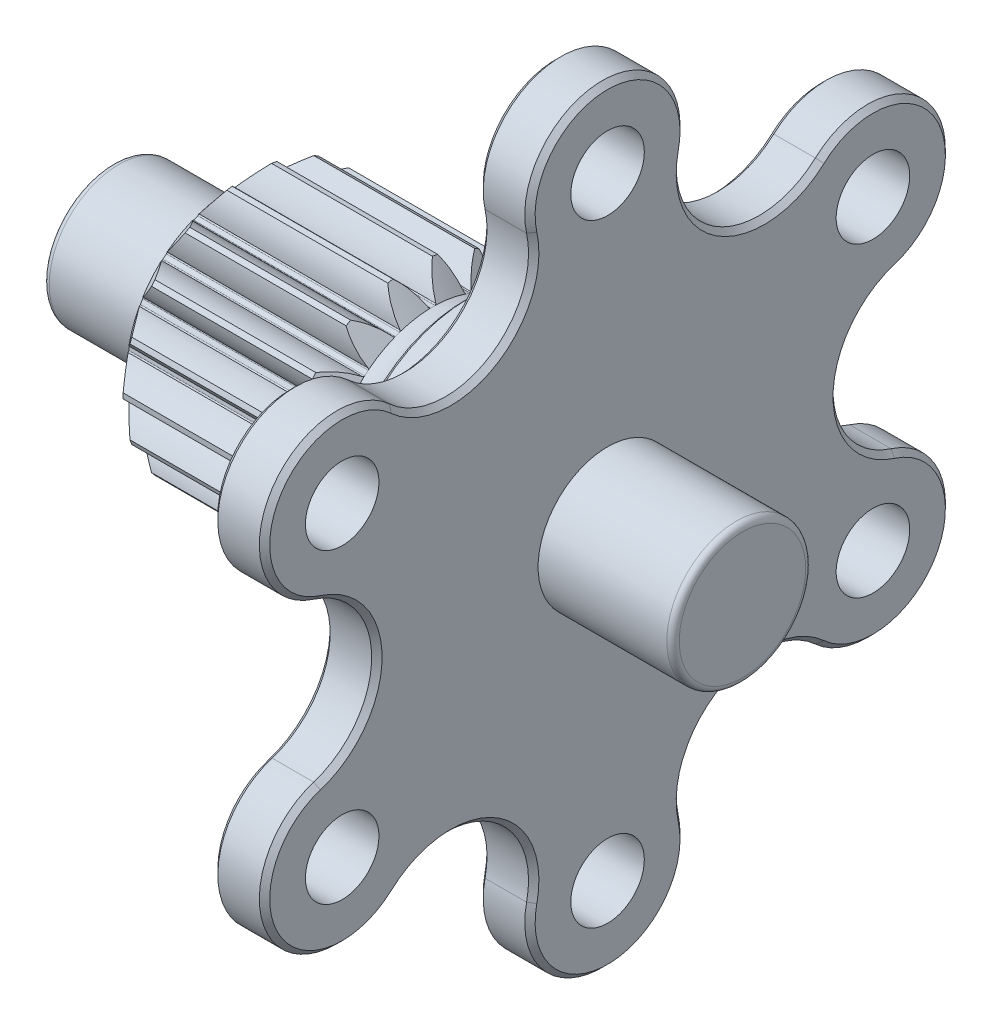
SolidWorks part; units mm, degrees
material "4140 Steel"
ref_plane "X-Y Datum" through (0, 0, 0) normal (0, 0, 1) x (1, 0, 0)
ref_plane "X-Z Datum" through (0, 0, 0) normal (0, 1, 0) x (1, 0, 0)
ref_plane "Y-Z Datum" through (0, 0, 0) normal (1, 0, 0) x (0, 0, -1)
sketch "Sketch1" plane through (0, 0, 0) normal (1, 0, 0) x (0, 0, -1)
  circle A0 centre (0, 0) radius 47
  dimension "D1" = 94
extrude "Base-Extrude" add sketch "Sketch1" against normal blind 6.35
hole_wizard "M8 Clearance Holes" positions "Sketch5" profile "Sketch7" hole size "M8" standard "ANSI Metric" end condition through all
sketch "Sketch5" plane through (0, 0, 0) normal (1, 0, 0) x (0, 0, -1)
  point P0 (0, -37.5)
  dimension "D1" = 37.5
sketch "Sketch7" plane through (0, -37.5, 0) normal (0, 1, 0) x (0, 0, -1)
  line L0 (0, 0) -> (0, 6.35)
  line L1 (0, 6.35) -> (4.5, 6.35)
  line L2 (4.5, 6.35) -> (4.5, 0)
  line L5 (4.5, 0) -> (0, 0)
  line L11 (0, -6.35) -> (0, 107.95) construction
  dimension "Thru Hole Dia." = 9
  dimension "Thru Hole Depth" = 6.35
pattern_circular "CirPattern" count 6 over 360 about axis through (-6.35, 0, 0) along (1, 0, 0) of "M8 Clearance Holes"
sketch "Sketch19" plane through (0, 0, 0) normal (1, 0, 0) x (0, 0, -1)
  line L0 (0, 37.5) -> (32.476, 18.75) construction
  circle A0 centre (0, 37.5) radius 9.5
  circle A1 centre (32.476, 18.75) radius 9.5
  circle A2 centre (0, 0) radius 47 construction
  arc A3 (9.2748, 35.4439) -> (26.0579, 25.7542) centre (19.194, 33.245) ccw
  circle A4 centre (32.476, 18.75) radius 9.5
  circle A5 centre (32.476, -18.75) radius 9.5
  arc A6 (35.3328, 9.6897) -> (35.3328, -9.6897) centre (38.3881, 0) ccw
  circle A7 centre (32.476, -18.75) radius 9.5
  circle A8 centre (0, -37.5) radius 9.5
  arc A9 (26.0579, -25.7542) -> (9.2748, -35.4439) centre (19.194, -33.245) ccw
  circle A10 centre (0, -37.5) radius 9.5
  circle A11 centre (-32.476, -18.75) radius 9.5
  arc A12 (-9.2748, -35.4439) -> (-26.0579, -25.7542) centre (-19.194, -33.245) ccw
  circle A13 centre (-32.476, -18.75) radius 9.5
  circle A14 centre (-32.476, 18.75) radius 9.5
  arc A15 (-35.3328, -9.6897) -> (-35.3328, 9.6897) centre (-38.3881, 0) ccw
  circle A16 centre (-32.476, 18.75) radius 9.5
  circle A17 centre (0, 37.5) radius 9.5
  arc A18 (-26.0579, 25.7542) -> (-9.2748, 35.4439) centre (-19.194, 33.245) ccw
  circle A19 centre (-32.476, 18.75) radius 4.5 construction
  circle M12 centre (0, 0) radius 47
  dimension "D1" = 10.16
  dimension "D2" = 6
extrude "Cut-Extrude" cut sketch "Sketch19" against normal through all both and the other way through all contours A16 A18 A0 M12 | A0 A3 A1 M12 | A13 A15 A14 M12 | A4 A6 A5 M12 | A7 A9 A8 M12 | A10 A12 A11 M12 | L0 A3 region at (0, 34.8675, -20.1307) region at (0, 26.6235, -15.3711) region at (0, 33.8688, 19.5541) region at (0, 0, -39.1083) region at (0, 0, 39.1083) region at (0, -33.8688, 19.5541) region at (0, -33.8688, -19.5541)
chamfer "Chamfer1" distance 0.635 angle 45 12 edges at (-6.35, 0, 28.2281) (-6.35, -23.5, 40.7032) (-6.35, 23.5, 40.7032) (-6.35, -24.4462, 14.114) (-6.35, 24.4462, 14.114) (-6.35, -47, 0) (-6.35, 47, 0) (-6.35, -24.4462, -14.114) (-6.35, -23.5, -40.7032) (-6.35, 0, -28.2281) (-6.35, 23.5, -40.7032) (-6.35, 24.4462, -14.114)
sketch "Sketch8" plane through (-6.35, 0, 0) normal (-1, 0, 0) x (0, 0, 1)
  circle A0 centre (0, 0) radius 15.748
  dimension "D1" = 31.496
extrude "Shaft-Extrude" add sketch "Sketch8" along normal blind 52.582
chamfer "Chamfer3" distance 0.635 angle 45 12 edges at (0, -23.5, 40.7032) (0, 0, 28.2281) (0, -24.4462, 14.114) (0, 23.5, 40.7032) (0, -47, 0) (0, 24.4462, 14.114) (0, -24.4462, -14.114) (0, 47, 0) (0, 24.4462, -14.114) (0, -23.5, -40.7032) (0, 0, -28.2281) (0, 23.5, -40.7032)
chamfer "Shaft Chamfer" distance 1 angle 45 1 edges at (-58.932, 0, 15.748)
sketch "Sketch45" plane through (-58.932, 0, 0) normal (-1, 0, 0) x (0, 0, 1)
  circle A0 centre (0, 0) radius 15.748 construction
  circle A1 centre (0, 0) radius 15.748
  circle A2 centre (0, 0) radius 8.5127
  dimension "D1" = 17.0254
extrude "Cut-Extrude1" cut sketch "Sketch45" against normal blind 12.857
chamfer "Chamfer4" [suppressed] distance 0.254 angle 45
sketch "Sketch51" [suppressed] plane through (-6.35, 0, 0) normal (-1, 0, 0) x (0, 0, 1)
  circle A2 centre (0, 0) radius 13.97
  circle A3 centre (0, 0) radius 13.97
  dimension "D1" = 0
extrude "Boss-Extrude1" [suppressed] add sketch "Sketch51" along normal blind 17.5
sketch "Sketch55" plane through (0, 0, 0) normal (1, 0, 0) x (0, 0, -1)
  circle A0 centre (0, 0) radius 8.5
  dimension "D1" = 17
extrude "Boss-Extrude4" add sketch "Sketch55" along normal blind 16.51
sketch "Sketch56" plane through (-58.932, 0, 0) normal (-1, 0, 0) x (0, 0, 1)
  circle A1 centre (0, 0) radius 8.5127
  circle A4 centre (0, 0) radius 8.5127
  dimension "D1" = 0
extrude "Boss-Extrude5" add sketch "Sketch56" along normal blind 1.643
sketch "Sketch22" [suppressed] plane through (-6.35, 0, 0) normal (-1, 0, 0) x (0, 0, 1)
  circle A0 centre (32.476, 18.75) radius 6.1
  circle A1 centre (32.476, -18.75) radius 6.1
  circle A2 centre (0, -37.5) radius 6.1
  circle A3 centre (0, 37.5) radius 6.1
  circle A4 centre (-32.476, 18.75) radius 6.1
  circle A5 centre (-32.476, -18.75) radius 6.1
  dimension "D1" = 12.2
split line "Split Line1" [suppressed]
split line "Split Line2"
sketch "Sketch22<2>" [suppressed] plane through (-6.35, 0, 0) normal (-1, 0, 0) x (0, 0, 1) same geometry as "Sketch22"
fillet "Fillet4" [suppressed] radius 1.5875
ref_plane "Plane3" [suppressed] through (0, 0, 12.7) normal (0, 0, 1) x (1, 0, 0)
sketch "Sketch48" [suppressed] plane through (0, 0, 12.7) normal (0, 0, 1) x (1, 0, 0)
  line L0 (-46.075, 12.446) -> (-46.075, -12.446) construction
  line L1 (-23.85, 3.175) -> (-46.075, 3.175)
  line L3 (-23.85, -3.175) -> (-46.075, -3.175)
  line L4 (-46.075, 3.175) -> (-46.075, -3.175)
  line L5 (-46.075, 12.446) -> (-46.075, -12.446)
  line L6 (-46.075, 0) -> (-12.2887, 0) construction
  line L7 (-23.85, 12.7) -> (-23.85, -12.7) construction
  arc A0 (-23.85, 3.175) -> (-23.85, -3.175) centre (-23.85, 0) cw
  dimension "D2" = 6.35
extrude "Cut-Extrude3" [suppressed] cut sketch "Sketch48" against normal blind 3.175 and the other way blind 17.5 contours L4 L6 A0 L1 | L6 L5 L3 A0
ref_plane "Plane4" [suppressed] through (0, 0, 13.97) normal (0, 0, 1) x (1, 0, 0)
fillet "Fillet5" [suppressed] radius 0.7937
sketch "Sketch57" [suppressed] plane through (-46.075, 0, 0) normal (-1, 0, 0) x (0, 0, 1)
  arc A0 (9.097, -5.6181) -> (9.7313, -4.4292) centre (0, 0) ccw
  arc A1 (9.097, -5.6181) -> (9.0986, -5.9863) centre (9.3955, -5.8008) ccw
  arc A2 (10.055, -4.164) -> (9.7313, -4.4292) centre (10.071, -4.5136) ccw
  arc A3 (12.1705, -3.6562) -> (12.3682, -3.3733) centre (12.0198, -3.3403) ccw
  arc A4 (12.3682, -3.3733) -> (12.5192, -2.7609) centre (0, 0) ccw
  arc A5 (9.3839, -8.7347) -> (9.8021, -8.2626) centre (0, 0) ccw
  arc A6 (4.2498, -12.0951) -> (4.8395, -11.8715) centre (0, 0) ccw
  arc A7 (-1.8579, -12.6847) -> (-1.2318, -12.7607) centre (0, 0) ccw
  arc A8 (-7.5399, -10.3683) -> (-7.0209, -10.7266) centre (0, 0) ccw
  arc A9 (-11.4947, -5.6767) -> (-11.2016, -6.2352) centre (0, 0) ccw
  arc A10 (-12.82, 0) -> (-12.8161, -0.3154) centre (0, 0) ccw
  arc A11 (12.5274, -2.6855) -> (12.4465, -2.4617) centre (12.1774, -2.6855) ccw
  arc A12 (12.5192, -2.7609) -> (12.5274, -2.6855) centre (12.1774, -2.6855) ccw
  arc A13 (10.6367, -0.7037) -> (10.8093, -1.029) centre (10.986, -0.7268) ccw
  arc A14 (10.6367, -0.7037) -> (10.66, 0) centre (0, 0) ccw
  arc A15 (10.66, 0) -> (10.6367, 0.7037) centre (0, 0) ccw
  arc A16 (10.8093, 1.029) -> (10.6367, 0.7037) centre (10.986, 0.7268) ccw
  arc A17 (12.4465, 2.4617) -> (12.5274, 2.6855) centre (12.1774, 2.6855) ccw
  arc A18 (-12.8161, 0.3154) -> (-12.82, 0) centre (0, 0) ccw
  arc A19 (-11.2016, 6.2352) -> (-11.4947, 5.6767) centre (0, 0) ccw
  arc A20 (-7.0209, 10.7266) -> (-7.5399, 10.3683) centre (0, 0) ccw
  arc A21 (-1.2318, 12.7607) -> (-1.8579, 12.6847) centre (0, 0) ccw
  arc A22 (4.8395, 11.8715) -> (4.2498, 12.0951) centre (0, 0) ccw
  arc A23 (9.8021, 8.2626) -> (9.3839, 8.7347) centre (0, 0) ccw
  arc A24 (12.5192, 2.7609) -> (12.3682, 3.3733) centre (0, 0) ccw
  arc A25 (12.5274, 2.6855) -> (12.5192, 2.7609) centre (12.1774, 2.6855) ccw
  arc A26 (12.3682, 3.3733) -> (12.1649, 3.6044) centre (12.0306, 3.2812) ccw
  arc A27 (9.7454, 4.32) -> (10.0494, 4.1122) centre (10.0654, 4.4619) ccw
  arc A28 (9.7454, 4.32) -> (9.0913, 5.5663) centre (0, 0) ccw
  arc A29 (9.093, 5.9345) -> (9.0913, 5.5663) centre (9.3898, 5.749) ccw
  arc A30 (9.8845, 8.037) -> (9.8021, 8.2626) centre (9.5345, 8.037) ccw
  arc A31 (9.8768, 7.9639) -> (9.8845, 8.037) centre (9.5345, 8.037) ccw
  arc A32 (9.3839, 8.7347) -> (9.0964, 8.8448) centre (9.1277, 8.4962) ccw
  arc A33 (6.6215, 8.3541) -> (5.4632, 9.1536) centre (0, 0) ccw
  arc A34 (6.6215, 8.3541) -> (6.9873, 8.3114) centre (6.8389, 8.6284) ccw
  arc A35 (5.2936, 9.4805) -> (5.4632, 9.1536) centre (5.6426, 9.4542) ccw
  arc A36 (5.0444, 11.6417) -> (4.8395, 11.8715) centre (4.7074, 11.5474) ccw
  arc A37 (4.2498, 12.0951) -> (3.9441, 12.059) centre (4.1338, 11.7649) ccw
  arc A38 (1.9807, 10.4744) -> (0.5835, 10.644) centre (0, 0) ccw
  arc A39 (1.9807, 10.4744) -> (2.3244, 10.6065) centre (2.0458, 10.8183) ccw
  arc A40 (0.2814, 10.8546) -> (0.5835, 10.644) centre (0.6027, 10.9935) ccw
  arc A41 (-0.9435, 12.6525) -> (-1.2318, 12.7607) centre (-1.1981, 12.4123) ccw
  arc A42 (-1.8579, 12.6847) -> (-2.1118, 12.5106) centre (-1.8071, 12.3384) ccw
  arc A43 (-3.1138, 10.1951) -> (-4.4298, 9.696) centre (0, 0) ccw
  arc A44 (-3.1138, 10.1951) -> (-2.8709, 10.4718) centre (-3.2161, 10.5298) ccw
  arc A45 (-4.7952, 9.742) -> (-4.4298, 9.696) centre (-4.5753, 10.0143) ccw
  arc A46 (-6.7154, 10.7647) -> (-7.0209, 10.7266) centre (-6.8292, 10.4338) ccw
  arc A47 (-7.5399, 10.3683) -> (-7.6839, 10.0962) centre (-7.3341, 10.0853) ccw
  arc A48 (-7.4951, 7.5802) -> (-7.3911, 7.8291) centre (-7.7411, 7.8291) ccw
  arc A49 (-7.4951, 7.5802) -> (-8.4284, 6.5267) centre (0, 0) ccw
  arc A50 (-7.3911, 7.8291) -> (-7.4086, 7.9381) centre (-7.7411, 7.8291) ccw
  arc A51 (-8.7733, 6.3977) -> (-8.4284, 6.5267) centre (-8.7051, 6.741) ccw
  arc A52 (-10.9488, 6.4109) -> (-11.2016, 6.2352) centre (-10.8957, 6.065) ccw
  arc A53 (-11.4947, 5.6767) -> (-11.4957, 5.3689) centre (-11.1808, 5.5217) ccw
  arc A54 (-10.1592, 3.2288) -> (-10.4961, 1.8623) centre (0, 0) ccw
  arc A55 (-10.1428, 3.3348) -> (-10.249, 3.5859) centre (-10.4928, 3.3348) ccw
  arc A56 (-10.1592, 3.2288) -> (-10.1428, 3.3348) centre (-10.4928, 3.3348) ccw
  arc A57 (-10.7415, 1.5877) -> (-10.4961, 1.8623) centre (-10.8407, 1.9234) ccw
  arc A58 (-12.674, 0.5884) -> (-12.8161, 0.3154) centre (-12.4662, 0.3067) ccw
  arc A59 (-12.8161, -0.3154) -> (-12.674, -0.5884) centre (-12.4662, -0.3067) ccw
  arc A60 (-10.4961, -1.8623) -> (-10.7415, -1.5877) centre (-10.8407, -1.9234) ccw
  arc A61 (-10.4961, -1.8623) -> (-10.1592, -3.2288) centre (0, 0) ccw
  arc A62 (-10.1428, -3.3348) -> (-10.1592, -3.2288) centre (-10.4928, -3.3348) ccw
  arc A63 (-10.249, -3.5859) -> (-10.1428, -3.3348) centre (-10.4928, -3.3348) ccw
  arc A64 (-11.4957, -5.3689) -> (-11.4947, -5.6767) centre (-11.1808, -5.5217) ccw
  arc A65 (-11.2016, -6.2352) -> (-10.9488, -6.4109) centre (-10.8957, -6.065) ccw
  arc A66 (-8.4284, -6.5267) -> (-8.7733, -6.3977) centre (-8.7051, -6.741) ccw
  arc A67 (-8.4284, -6.5267) -> (-7.4951, -7.5802) centre (0, 0) ccw
  arc A68 (-7.3911, -7.8291) -> (-7.4951, -7.5802) centre (-7.7411, -7.8291) ccw
  arc A69 (-7.4086, -7.9381) -> (-7.3911, -7.8291) centre (-7.7411, -7.8291) ccw
  arc A70 (-7.6839, -10.0962) -> (-7.5399, -10.3683) centre (-7.3341, -10.0853) ccw
  arc A71 (-7.0209, -10.7266) -> (-6.7154, -10.7647) centre (-6.8292, -10.4338) ccw
  arc A72 (-4.4298, -9.696) -> (-4.7952, -9.742) centre (-4.5753, -10.0143) ccw
  arc A73 (-4.4298, -9.696) -> (-3.1138, -10.1951) centre (0, 0) ccw
  arc A74 (-2.8709, -10.4718) -> (-3.1138, -10.1951) centre (-3.2161, -10.5298) ccw
  arc A75 (-2.1118, -12.5106) -> (-1.8579, -12.6847) centre (-1.8071, -12.3384) ccw
  arc A76 (-1.2318, -12.7607) -> (-0.9435, -12.6525) centre (-1.1981, -12.4123) ccw
  arc A77 (0.5835, -10.644) -> (1.9807, -10.4744) centre (0, 0) ccw
  arc A78 (0.5835, -10.644) -> (0.2814, -10.8546) centre (0.6027, -10.9935) ccw
  arc A79 (2.3244, -10.6065) -> (1.9807, -10.4744) centre (2.0458, -10.8183) ccw
  arc A80 (3.9441, -12.059) -> (4.2498, -12.0951) centre (4.1338, -11.7649) ccw
  arc A81 (4.8395, -11.8715) -> (5.0444, -11.6417) centre (4.7074, -11.5474) ccw
  arc A82 (5.4632, -9.1536) -> (5.2936, -9.4805) centre (5.6426, -9.4542) ccw
  arc A83 (5.4632, -9.1536) -> (6.6215, -8.3541) centre (0, 0) ccw
  arc A84 (6.9873, -8.3114) -> (6.6215, -8.3541) centre (6.8389, -8.6284) ccw
  arc A85 (9.0964, -8.8448) -> (9.3839, -8.7347) centre (9.1277, -8.4962) ccw
  arc A86 (9.8021, -8.2626) -> (9.8901, -8.0888) centre (9.5462, -8.0238) ccw
  arc A87 (9.8901, -8.0888) -> (9.8824, -8.0157) centre (9.5401, -8.0888) ccw
  circle A88 centre (0, 0) radius 13.97 construction
  circle A89 centre (0, 0) radius 13.97
  spline S0 degree 4 poles (9.0986, -5.9863) (9.1513, -6.0706) (9.2437, -6.2285) (9.367, -6.4648) (9.5091, -6.7844) (9.6282, -7.0962) (9.741, -7.4422) (9.814, -7.7129) (9.8587, -7.9047) (9.8824, -8.0157) knots 0 0 0 0 0 0.181969 0.334561 0.487154 0.639745 0.792337 1 1 1 1 1 weights 1 1 1 1 1 1 1 1 1 1
  spline S1 degree 4 poles (10.055, -4.164) (10.1544, -4.1595) (10.3368, -4.1458) (10.6013, -4.113) (10.9451, -4.0484) (11.2693, -3.9693) (11.6181, -3.8656) (11.8824, -3.7718) (12.0657, -3.6997) (12.1705, -3.6562) knots 0 0 0 0 0 0.181969 0.334561 0.487154 0.639745 0.792337 1 1 1 1 1 weights 1 1 1 1 1 1 1 1 1 1
  spline S2 degree 4 poles (10.8093, -1.029) (10.8952, -1.0792) (11.0504, -1.176) (11.2693, -1.328) (11.5437, -1.545) (11.7941, -1.7657) (12.0547, -2.0196) (12.2452, -2.2255) (12.3739, -2.3745) (12.4465, -2.4617) knots 0 0 0 0 0 0.181969 0.334561 0.487154 0.639745 0.792337 1 1 1 1 1 weights 1 1 1 1 1 1 1 1 1 1
  spline S3 degree 4 poles (10.8093, 1.029) (10.8952, 1.0792) (11.0504, 1.176) (11.2693, 1.328) (11.5437, 1.545) (11.7941, 1.7657) (12.0547, 2.0196) (12.2452, 2.2255) (12.3739, 2.3745) (12.4465, 2.4617) knots 0 0 0 0 0 0.181969 0.334561 0.487154 0.639745 0.792337 1 1 1 1 1 weights 1 1 1 1 1 1 1 1 1 1
  spline S4 degree 4 poles (10.0494, 4.1122) (10.1488, 4.1077) (10.3312, 4.094) (10.5956, 4.0613) (10.9394, 3.9966) (11.2637, 3.9175) (11.6125, 3.8138) (11.8768, 3.7201) (12.06, 3.648) (12.1649, 3.6044) knots 0 0 0 0 0 0.181969 0.334561 0.487154 0.639745 0.792337 1 1 1 1 1 weights 1 1 1 1 1 1 1 1 1 1
  spline S5 degree 4 poles (9.093, 5.9345) (9.1457, 6.0188) (9.2381, 6.1767) (9.3613, 6.413) (9.5035, 6.7326) (9.6225, 7.0445) (9.7353, 7.3904) (9.8083, 7.6612) (9.8531, 7.8529) (9.8768, 7.9639) knots 0 0 0 0 0 0.181969 0.334561 0.487154 0.639745 0.792337 1 1 1 1 1 weights 1 1 1 1 1 1 1 1 1 1
  spline S6 degree 4 poles (6.9873, 8.3114) (7.0773, 8.3535) (7.2452, 8.4262) (7.4946, 8.5201) (7.8291, 8.6227) (8.153, 8.7033) (8.51, 8.7735) (8.7876, 8.8134) (8.9833, 8.8347) (9.0964, 8.8448) knots 0 0 0 0 0 0.181969 0.334561 0.487154 0.639745 0.792337 1 1 1 1 1 weights 1 1 1 1 1 1 1 1 1 1
  spline S7 degree 4 poles (5.2936, 9.4805) (5.301, 9.5796) (5.3095, 9.7624) (5.3088, 10.0288) (5.2861, 10.3779) (5.2466, 10.7094) (5.1857, 11.0681) (5.1245, 11.3418) (5.075, 11.5324) (5.0444, 11.6417) knots 0 0 0 0 0 0.181969 0.334561 0.487154 0.639745 0.792337 1 1 1 1 1 weights 1 1 1 1 1 1 1 1 1 1
  spline S8 degree 4 poles (2.3244, 10.6065) (2.3846, 10.6857) (2.4995, 10.8281) (2.6767, 11.0271) (2.9252, 11.2733) (3.1745, 11.4952) (3.4579, 11.7234) (3.6852, 11.8876) (3.8487, 11.9975) (3.9441, 12.059) knots 0 0 0 0 0 0.181969 0.334561 0.487154 0.639745 0.792337 1 1 1 1 1 weights 1 1 1 1 1 1 1 1 1 1
  spline S9 degree 4 poles (0.2814, 10.8546) (0.2419, 10.9458) (0.1645, 11.1116) (0.0401, 11.3472) (-0.1423, 11.6458) (-0.3313, 11.9209) (-0.5519, 12.2102) (-0.7332, 12.4241) (-0.8657, 12.5699) (-0.9435, 12.6525) knots 0 0 0 0 0 0.181969 0.334561 0.487154 0.639745 0.792337 1 1 1 1 1 weights 1 1 1 1 1 1 1 1 1 1
  spline S10 degree 4 poles (-2.8709, 10.4718) (-2.8544, 10.5699) (-2.8189, 10.7493) (-2.7545, 11.0079) (-2.6489, 11.3414) (-2.5312, 11.6538) (-2.3863, 11.9875) (-2.2613, 12.2386) (-2.1677, 12.4118) (-2.1118, 12.5106) knots 0 0 0 0 0 0.181969 0.334561 0.487154 0.639745 0.792337 1 1 1 1 1 weights 1 1 1 1 1 1 1 1 1 1
  spline S11 degree 4 poles (-4.7952, 9.742) (-4.8726, 9.8045) (-5.0181, 9.9153) (-5.2378, 10.0661) (-5.538, 10.2457) (-5.8332, 10.4015) (-6.163, 10.5552) (-6.423, 10.6603) (-6.608, 10.7278) (-6.7154, 10.7647) knots 0 0 0 0 0 0.181969 0.334561 0.487154 0.639745 0.792337 1 1 1 1 1 weights 1 1 1 1 1 1 1 1 1 1
  spline S12 degree 4 poles (-7.4086, 7.9381) (-7.4395, 8.0326) (-7.4915, 8.2081) (-7.5546, 8.4669) (-7.6161, 8.8113) (-7.6571, 9.1426) (-7.6838, 9.5054) (-7.6899, 9.7858) (-7.6874, 9.9827) (-7.6839, 10.0962) knots 0 0 0 0 0 0.181969 0.334561 0.487154 0.639745 0.792337 1 1 1 1 1 weights 1 1 1 1 1 1 1 1 1 1
  spline S13 degree 4 poles (-8.7733, 6.3977) (-8.8708, 6.4171) (-9.0512, 6.4475) (-9.3158, 6.4789) (-9.6651, 6.4985) (-9.9989, 6.4992) (-10.3623, 6.482) (-10.6414, 6.4543) (-10.8366, 6.4281) (-10.9488, 6.4109) knots 0 0 0 0 0 0.181969 0.334561 0.487154 0.639745 0.792337 1 1 1 1 1 weights 1 1 1 1 1 1 1 1 1 1
  spline S14 degree 4 poles (-10.249, 3.5859) (-10.3203, 3.6552) (-10.4478, 3.7864) (-10.624, 3.9863) (-10.8386, 4.2627) (-11.0288, 4.5369) (-11.2211, 4.8458) (-11.3567, 5.0913) (-11.4461, 5.2667) (-11.4957, 5.3689) knots 0 0 0 0 0 0.181969 0.334561 0.487154 0.639745 0.792337 1 1 1 1 1 weights 1 1 1 1 1 1 1 1 1 1
  spline S15 degree 4 poles (-10.7415, 1.5877) (-10.8369, 1.5596) (-11.0107, 1.5027) (-11.2597, 1.4075) (-11.578, 1.2625) (-11.8739, 1.1081) (-12.1877, 0.9239) (-12.4219, 0.7697) (-12.5826, 0.6558) (-12.674, 0.5884) knots 0 0 0 0 0 0.181969 0.334561 0.487154 0.639745 0.792337 1 1 1 1 1 weights 1 1 1 1 1 1 1 1 1 1
  spline S16 degree 4 poles (-10.7415, -1.5877) (-10.8369, -1.5596) (-11.0107, -1.5027) (-11.2597, -1.4075) (-11.578, -1.2625) (-11.8739, -1.1081) (-12.1877, -0.9239) (-12.4219, -0.7697) (-12.5826, -0.6558) (-12.674, -0.5884) knots 0 0 0 0 0 0.181969 0.334561 0.487154 0.639745 0.792337 1 1 1 1 1 weights 1 1 1 1 1 1 1 1 1 1
  spline S17 degree 4 poles (-10.249, -3.5859) (-10.3203, -3.6552) (-10.4478, -3.7864) (-10.624, -3.9863) (-10.8386, -4.2627) (-11.0288, -4.5369) (-11.2211, -4.8458) (-11.3567, -5.0913) (-11.4461, -5.2667) (-11.4957, -5.3689) knots 0 0 0 0 0 0.181969 0.334561 0.487154 0.639745 0.792337 1 1 1 1 1 weights 1 1 1 1 1 1 1 1 1 1
  spline S18 degree 4 poles (-8.7733, -6.3977) (-8.8708, -6.4171) (-9.0512, -6.4475) (-9.3158, -6.4789) (-9.6651, -6.4985) (-9.9989, -6.4992) (-10.3623, -6.482) (-10.6414, -6.4543) (-10.8366, -6.4281) (-10.9488, -6.4109) knots 0 0 0 0 0 0.181969 0.334561 0.487154 0.639745 0.792337 1 1 1 1 1 weights 1 1 1 1 1 1 1 1 1 1
  spline S19 degree 4 poles (-7.4086, -7.9381) (-7.4395, -8.0326) (-7.4915, -8.2081) (-7.5546, -8.4669) (-7.6161, -8.8113) (-7.6571, -9.1426) (-7.6838, -9.5054) (-7.6899, -9.7858) (-7.6874, -9.9827) (-7.6839, -10.0962) knots 0 0 0 0 0 0.181969 0.334561 0.487154 0.639745 0.792337 1 1 1 1 1 weights 1 1 1 1 1 1 1 1 1 1
  spline S20 degree 4 poles (-4.7952, -9.742) (-4.8726, -9.8045) (-5.0181, -9.9153) (-5.2378, -10.0661) (-5.538, -10.2457) (-5.8332, -10.4015) (-6.163, -10.5552) (-6.423, -10.6603) (-6.608, -10.7278) (-6.7154, -10.7647) knots 0 0 0 0 0 0.181969 0.334561 0.487154 0.639745 0.792337 1 1 1 1 1 weights 1 1 1 1 1 1 1 1 1 1
  spline S21 degree 4 poles (-2.8709, -10.4718) (-2.8544, -10.5699) (-2.8189, -10.7493) (-2.7545, -11.0079) (-2.6489, -11.3414) (-2.5312, -11.6538) (-2.3863, -11.9875) (-2.2613, -12.2386) (-2.1677, -12.4118) (-2.1118, -12.5106) knots 0 0 0 0 0 0.181969 0.334561 0.487154 0.639745 0.792337 1 1 1 1 1 weights 1 1 1 1 1 1 1 1 1 1
  spline S22 degree 4 poles (0.2814, -10.8546) (0.2419, -10.9458) (0.1645, -11.1116) (0.0401, -11.3472) (-0.1423, -11.6458) (-0.3313, -11.9209) (-0.5519, -12.2102) (-0.7332, -12.4241) (-0.8657, -12.5699) (-0.9435, -12.6525) knots 0 0 0 0 0 0.181969 0.334561 0.487154 0.639745 0.792337 1 1 1 1 1 weights 1 1 1 1 1 1 1 1 1 1
  spline S23 degree 4 poles (2.3244, -10.6065) (2.3846, -10.6857) (2.4995, -10.8281) (2.6767, -11.0271) (2.9252, -11.2733) (3.1745, -11.4952) (3.4579, -11.7234) (3.6852, -11.8876) (3.8487, -11.9975) (3.9441, -12.059) knots 0 0 0 0 0 0.181969 0.334561 0.487154 0.639745 0.792337 1 1 1 1 1 weights 1 1 1 1 1 1 1 1 1 1
  spline S24 degree 4 poles (5.2936, -9.4805) (5.301, -9.5796) (5.3095, -9.7624) (5.3088, -10.0288) (5.2861, -10.3779) (5.2466, -10.7094) (5.1857, -11.0681) (5.1245, -11.3418) (5.075, -11.5324) (5.0444, -11.6417) knots 0 0 0 0 0 0.181969 0.334561 0.487154 0.639745 0.792337 1 1 1 1 1 weights 1 1 1 1 1 1 1 1 1 1
  spline S25 degree 4 poles (6.9873, -8.3114) (7.0773, -8.3535) (7.2452, -8.4262) (7.4946, -8.5201) (7.8291, -8.6227) (8.153, -8.7033) (8.51, -8.7735) (8.7876, -8.8134) (8.9833, -8.8347) (9.0964, -8.8448) knots 0 0 0 0 0 0.181969 0.334561 0.487154 0.639745 0.792337 1 1 1 1 1 weights 1 1 1 1 1 1 1 1 1 1
extrude "Cut-Extrude6" [suppressed] cut sketch "Sketch57" against normal blind 22.225
sketch "Sketch58" [suppressed] plane through (-23.85, 0, 0) normal (-1, 0, 0) x (0, 0, 1)
  circle A0 centre (0, 0) radius 12.7679
  circle A1 centre (0, 0) radius 13.97 construction
  circle A2 centre (0, 0) radius 13.97
extrude "Cut-Extrude7" [suppressed] cut sketch "Sketch58" against normal up to surface (17.5 mm away) up to face at (-6.35, 0, -15.748)
sketch "Sketch59" [suppressed] plane through (-23.85, 0, 0) normal (-1, 0, 0) x (0, 0, 1)
  circle A1 centre (0, 0) radius 12.7679 construction
  circle A2 centre (0, 0) radius 12.7679
  circle A7 centre (0, 0) radius 10.541
  dimension "D1" = 21.082
extrude "Cut-Extrude10" [suppressed] cut sketch "Sketch59" against normal blind 3.175
chamfer "Chamfer5" [suppressed] distance 1.524 angle 45
sketch "Sketch65" [suppressed] plane through (-46.075, 0, 0) normal (-1, 0, 0) x (0, 0, 1)
  arc A3 (9.097, -5.6181) -> (9.0986, -5.9863) centre (9.3955, -5.8008) ccw
  arc A84 (9.097, -5.6181) -> (9.0986, -5.9863) centre (9.3955, -5.8008) ccw
  arc A85 (9.097, -5.6181) -> (9.7313, -4.4292) centre (0, 0) ccw
  arc A86 (9.097, -5.6181) -> (9.7313, -4.4292) centre (0, 0) ccw
  arc A87 (10.055, -4.164) -> (9.7313, -4.4292) centre (10.071, -4.5136) ccw
  arc A88 (10.055, -4.164) -> (9.7313, -4.4292) centre (10.071, -4.5136) ccw
  arc A89 (12.1705, -3.6562) -> (12.3682, -3.3733) centre (12.0198, -3.3403) ccw
  arc A90 (12.1705, -3.6562) -> (12.3682, -3.3733) centre (12.0198, -3.3403) ccw
  arc A91 (12.3682, -3.3733) -> (12.5192, -2.7609) centre (0, 0) ccw
  arc A92 (12.3682, -3.3733) -> (12.5192, -2.7609) centre (0, 0) ccw
  arc A93 (12.5192, -2.7609) -> (12.4465, -2.4617) centre (12.1774, -2.6855) ccw
  arc A94 (12.5192, -2.7609) -> (12.4465, -2.4617) centre (12.1774, -2.6855) ccw
  arc A95 (10.6367, -0.7037) -> (10.8093, -1.029) centre (10.986, -0.7268) ccw
  arc A96 (10.6367, -0.7037) -> (10.8093, -1.029) centre (10.986, -0.7268) ccw
  arc A97 (10.6367, -0.7037) -> (10.6367, 0.7037) centre (0, 0) ccw
  arc A98 (10.6367, -0.7037) -> (10.6367, 0.7037) centre (0, 0) ccw
  arc A99 (10.8093, 1.029) -> (10.6367, 0.7037) centre (10.986, 0.7268) ccw
  arc A100 (10.8093, 1.029) -> (10.6367, 0.7037) centre (10.986, 0.7268) ccw
  arc A101 (12.4465, 2.4617) -> (12.5192, 2.7609) centre (12.1774, 2.6855) ccw
  arc A102 (12.4465, 2.4617) -> (12.5192, 2.7609) centre (12.1774, 2.6855) ccw
  arc A103 (12.5192, 2.7609) -> (12.3682, 3.3733) centre (0, 0) ccw
  arc A104 (12.5192, 2.7609) -> (12.3682, 3.3733) centre (0, 0) ccw
  arc A105 (12.3682, 3.3733) -> (12.1649, 3.6044) centre (12.0306, 3.2812) ccw
  arc A106 (12.3682, 3.3733) -> (12.1649, 3.6044) centre (12.0306, 3.2812) ccw
  arc A107 (9.7454, 4.32) -> (10.0494, 4.1122) centre (10.0654, 4.4619) ccw
  arc A108 (9.7454, 4.32) -> (10.0494, 4.1122) centre (10.0654, 4.4619) ccw
  arc A109 (9.7454, 4.32) -> (9.0913, 5.5663) centre (0, 0) ccw
  arc A110 (9.7454, 4.32) -> (9.0913, 5.5663) centre (0, 0) ccw
  arc A111 (9.093, 5.9345) -> (9.0913, 5.5663) centre (9.3898, 5.749) ccw
  arc A112 (9.093, 5.9345) -> (9.0913, 5.5663) centre (9.3898, 5.749) ccw
  arc A113 (9.8768, 7.9639) -> (9.8021, 8.2626) centre (9.5345, 8.037) ccw
  arc A114 (9.8768, 7.9639) -> (9.8021, 8.2626) centre (9.5345, 8.037) ccw
  arc A115 (9.8021, 8.2626) -> (9.3839, 8.7347) centre (0, 0) ccw
  arc A116 (9.8021, 8.2626) -> (9.3839, 8.7347) centre (0, 0) ccw
  arc A117 (9.3839, 8.7347) -> (9.0964, 8.8448) centre (9.1277, 8.4962) ccw
  arc A118 (9.3839, 8.7347) -> (9.0964, 8.8448) centre (9.1277, 8.4962) ccw
  arc A119 (6.6215, 8.3541) -> (6.9873, 8.3114) centre (6.8389, 8.6284) ccw
  arc A120 (6.6215, 8.3541) -> (6.9873, 8.3114) centre (6.8389, 8.6284) ccw
  arc A121 (6.6215, 8.3541) -> (5.4632, 9.1536) centre (0, 0) ccw
  arc A122 (6.6215, 8.3541) -> (5.4632, 9.1536) centre (0, 0) ccw
  arc A123 (5.2936, 9.4805) -> (5.4632, 9.1536) centre (5.6426, 9.4542) ccw
  arc A124 (5.2936, 9.4805) -> (5.4632, 9.1536) centre (5.6426, 9.4542) ccw
  arc A125 (5.0444, 11.6417) -> (4.8395, 11.8715) centre (4.7074, 11.5474) ccw
  arc A126 (5.0444, 11.6417) -> (4.8395, 11.8715) centre (4.7074, 11.5474) ccw
  arc A127 (4.8395, 11.8715) -> (4.2498, 12.0951) centre (0, 0) ccw
  arc A128 (4.8395, 11.8715) -> (4.2498, 12.0951) centre (0, 0) ccw
  arc A129 (4.2498, 12.0951) -> (3.9441, 12.059) centre (4.1338, 11.7649) ccw
  arc A130 (4.2498, 12.0951) -> (3.9441, 12.059) centre (4.1338, 11.7649) ccw
  arc A131 (1.9807, 10.4744) -> (2.3244, 10.6065) centre (2.0458, 10.8183) ccw
  arc A132 (1.9807, 10.4744) -> (2.3244, 10.6065) centre (2.0458, 10.8183) ccw
  arc A133 (1.9807, 10.4744) -> (0.5835, 10.644) centre (0, 0) ccw
  arc A134 (1.9807, 10.4744) -> (0.5835, 10.644) centre (0, 0) ccw
  arc A135 (0.2814, 10.8546) -> (0.5835, 10.644) centre (0.6027, 10.9935) ccw
  arc A136 (0.2814, 10.8546) -> (0.5835, 10.644) centre (0.6027, 10.9935) ccw
  arc A137 (-0.9435, 12.6525) -> (-1.2318, 12.7607) centre (-1.1981, 12.4123) ccw
  arc A138 (-0.9435, 12.6525) -> (-1.2318, 12.7607) centre (-1.1981, 12.4123) ccw
  arc A139 (-1.2318, 12.7607) -> (-1.8579, 12.6847) centre (0, 0) ccw
  arc A140 (-1.2318, 12.7607) -> (-1.8579, 12.6847) centre (0, 0) ccw
  arc A141 (-1.8579, 12.6847) -> (-2.1118, 12.5106) centre (-1.8071, 12.3384) ccw
  arc A142 (-1.8579, 12.6847) -> (-2.1118, 12.5106) centre (-1.8071, 12.3384) ccw
  arc A143 (-3.1138, 10.1951) -> (-2.8709, 10.4718) centre (-3.2161, 10.5298) ccw
  arc A144 (-3.1138, 10.1951) -> (-2.8709, 10.4718) centre (-3.2161, 10.5298) ccw
  arc A145 (-3.1138, 10.1951) -> (-4.4298, 9.696) centre (0, 0) ccw
  arc A146 (-3.1138, 10.1951) -> (-4.4298, 9.696) centre (0, 0) ccw
  arc A147 (-4.7952, 9.742) -> (-4.4298, 9.696) centre (-4.5753, 10.0143) ccw
  arc A148 (-4.7952, 9.742) -> (-4.4298, 9.696) centre (-4.5753, 10.0143) ccw
  arc A149 (-6.7154, 10.7647) -> (-7.0209, 10.7266) centre (-6.8292, 10.4338) ccw
  arc A150 (-6.7154, 10.7647) -> (-7.0209, 10.7266) centre (-6.8292, 10.4338) ccw
  arc A151 (-7.0209, 10.7266) -> (-7.5399, 10.3683) centre (0, 0) ccw
  arc A152 (-7.0209, 10.7266) -> (-7.5399, 10.3683) centre (0, 0) ccw
  arc A153 (-7.5399, 10.3683) -> (-7.6839, 10.0962) centre (-7.3341, 10.0853) ccw
  arc A154 (-7.5399, 10.3683) -> (-7.6839, 10.0962) centre (-7.3341, 10.0853) ccw
  arc A155 (-7.4951, 7.5802) -> (-7.4086, 7.9381) centre (-7.7411, 7.8291) ccw
  arc A156 (-7.4951, 7.5802) -> (-7.4086, 7.9381) centre (-7.7411, 7.8291) ccw
  arc A157 (-7.4951, 7.5802) -> (-8.4284, 6.5267) centre (0, 0) ccw
  arc A158 (-7.4951, 7.5802) -> (-8.4284, 6.5267) centre (0, 0) ccw
  arc A159 (-8.7733, 6.3977) -> (-8.4284, 6.5267) centre (-8.7051, 6.741) ccw
  arc A160 (-8.7733, 6.3977) -> (-8.4284, 6.5267) centre (-8.7051, 6.741) ccw
  arc A161 (-10.9488, 6.4109) -> (-11.2016, 6.2352) centre (-10.8957, 6.065) ccw
  arc A162 (-10.9488, 6.4109) -> (-11.2016, 6.2352) centre (-10.8957, 6.065) ccw
  arc A163 (-11.2016, 6.2352) -> (-11.4947, 5.6767) centre (0, 0) ccw
  arc A164 (-11.2016, 6.2352) -> (-11.4947, 5.6767) centre (0, 0) ccw
  arc A165 (-11.4947, 5.6767) -> (-11.4957, 5.3689) centre (-11.1808, 5.5217) ccw
  arc A166 (-11.4947, 5.6767) -> (-11.4957, 5.3689) centre (-11.1808, 5.5217) ccw
  arc A167 (-10.1592, 3.2288) -> (-10.249, 3.5859) centre (-10.4928, 3.3348) ccw
  arc A168 (-10.1592, 3.2288) -> (-10.249, 3.5859) centre (-10.4928, 3.3348) ccw
  arc A169 (-10.1592, 3.2288) -> (-10.4961, 1.8623) centre (0, 0) ccw
  arc A170 (-10.1592, 3.2288) -> (-10.4961, 1.8623) centre (0, 0) ccw
  arc A171 (-10.7415, 1.5877) -> (-10.4961, 1.8623) centre (-10.8407, 1.9234) ccw
  arc A172 (-10.7415, 1.5877) -> (-10.4961, 1.8623) centre (-10.8407, 1.9234) ccw
  arc A173 (-12.674, 0.5884) -> (-12.8161, 0.3154) centre (-12.4662, 0.3067) ccw
  arc A174 (-12.674, 0.5884) -> (-12.8161, 0.3154) centre (-12.4662, 0.3067) ccw
  arc A175 (-12.8161, 0.3154) -> (-12.8161, -0.3154) centre (0, 0) ccw
  arc A176 (-12.8161, 0.3154) -> (-12.8161, -0.3154) centre (0, 0) ccw
  arc A177 (-12.8161, -0.3154) -> (-12.674, -0.5884) centre (-12.4662, -0.3067) ccw
  arc A178 (-12.8161, -0.3154) -> (-12.674, -0.5884) centre (-12.4662, -0.3067) ccw
  arc A179 (-10.4961, -1.8623) -> (-10.7415, -1.5877) centre (-10.8407, -1.9234) ccw
  arc A180 (-10.4961, -1.8623) -> (-10.7415, -1.5877) centre (-10.8407, -1.9234) ccw
  arc A181 (-10.4961, -1.8623) -> (-10.1592, -3.2288) centre (0, 0) ccw
  arc A182 (-10.4961, -1.8623) -> (-10.1592, -3.2288) centre (0, 0) ccw
  arc A183 (-10.249, -3.5859) -> (-10.1592, -3.2288) centre (-10.4928, -3.3348) ccw
  arc A184 (-10.249, -3.5859) -> (-10.1592, -3.2288) centre (-10.4928, -3.3348) ccw
  arc A185 (-11.4957, -5.3689) -> (-11.4947, -5.6767) centre (-11.1808, -5.5217) ccw
  arc A186 (-11.4957, -5.3689) -> (-11.4947, -5.6767) centre (-11.1808, -5.5217) ccw
  arc A187 (-11.4947, -5.6767) -> (-11.2016, -6.2352) centre (0, 0) ccw
  arc A188 (-11.4947, -5.6767) -> (-11.2016, -6.2352) centre (0, 0) ccw
  arc A189 (-11.2016, -6.2352) -> (-10.9488, -6.4109) centre (-10.8957, -6.065) ccw
  arc A190 (-11.2016, -6.2352) -> (-10.9488, -6.4109) centre (-10.8957, -6.065) ccw
  arc A191 (-8.4284, -6.5267) -> (-8.7733, -6.3977) centre (-8.7051, -6.741) ccw
  arc A192 (-8.4284, -6.5267) -> (-8.7733, -6.3977) centre (-8.7051, -6.741) ccw
  arc A193 (-8.4284, -6.5267) -> (-7.4951, -7.5802) centre (0, 0) ccw
  arc A194 (-8.4284, -6.5267) -> (-7.4951, -7.5802) centre (0, 0) ccw
  arc A195 (-7.4086, -7.9381) -> (-7.4951, -7.5802) centre (-7.7411, -7.8291) ccw
  arc A196 (-7.4086, -7.9381) -> (-7.4951, -7.5802) centre (-7.7411, -7.8291) ccw
  arc A197 (-7.6839, -10.0962) -> (-7.5399, -10.3683) centre (-7.3341, -10.0853) ccw
  arc A198 (-7.6839, -10.0962) -> (-7.5399, -10.3683) centre (-7.3341, -10.0853) ccw
  arc A199 (-7.5399, -10.3683) -> (-7.0209, -10.7266) centre (0, 0) ccw
  arc A200 (-7.5399, -10.3683) -> (-7.0209, -10.7266) centre (0, 0) ccw
  arc A201 (-7.0209, -10.7266) -> (-6.7154, -10.7647) centre (-6.8292, -10.4338) ccw
  arc A202 (-7.0209, -10.7266) -> (-6.7154, -10.7647) centre (-6.8292, -10.4338) ccw
  arc A203 (-4.4298, -9.696) -> (-4.7952, -9.742) centre (-4.5753, -10.0143) ccw
  arc A204 (-4.4298, -9.696) -> (-4.7952, -9.742) centre (-4.5753, -10.0143) ccw
  arc A205 (-4.4298, -9.696) -> (-3.1138, -10.1951) centre (0, 0) ccw
  arc A206 (-4.4298, -9.696) -> (-3.1138, -10.1951) centre (0, 0) ccw
  arc A207 (-2.8709, -10.4718) -> (-3.1138, -10.1951) centre (-3.2161, -10.5298) ccw
  arc A208 (-2.8709, -10.4718) -> (-3.1138, -10.1951) centre (-3.2161, -10.5298) ccw
  arc A209 (-2.1118, -12.5106) -> (-1.8579, -12.6847) centre (-1.8071, -12.3384) ccw
  arc A210 (-2.1118, -12.5106) -> (-1.8579, -12.6847) centre (-1.8071, -12.3384) ccw
  arc A211 (-1.8579, -12.6847) -> (-1.2318, -12.7607) centre (0, 0) ccw
  arc A212 (-1.8579, -12.6847) -> (-1.2318, -12.7607) centre (0, 0) ccw
  arc A213 (-1.2318, -12.7607) -> (-0.9435, -12.6525) centre (-1.1981, -12.4123) ccw
  arc A214 (-1.2318, -12.7607) -> (-0.9435, -12.6525) centre (-1.1981, -12.4123) ccw
  arc A215 (0.5835, -10.644) -> (0.2814, -10.8546) centre (0.6027, -10.9935) ccw
  arc A216 (0.5835, -10.644) -> (0.2814, -10.8546) centre (0.6027, -10.9935) ccw
  arc A217 (0.5835, -10.644) -> (1.9807, -10.4744) centre (0, 0) ccw
  arc A218 (0.5835, -10.644) -> (1.9807, -10.4744) centre (0, 0) ccw
  arc A219 (2.3244, -10.6065) -> (1.9807, -10.4744) centre (2.0458, -10.8183) ccw
  arc A220 (2.3244, -10.6065) -> (1.9807, -10.4744) centre (2.0458, -10.8183) ccw
  arc A221 (3.9441, -12.059) -> (4.2498, -12.0951) centre (4.1338, -11.7649) ccw
  arc A222 (3.9441, -12.059) -> (4.2498, -12.0951) centre (4.1338, -11.7649) ccw
  arc A223 (4.2498, -12.0951) -> (4.8395, -11.8715) centre (0, 0) ccw
  arc A224 (4.2498, -12.0951) -> (4.8395, -11.8715) centre (0, 0) ccw
  arc A225 (4.8395, -11.8715) -> (5.0444, -11.6417) centre (4.7074, -11.5474) ccw
  arc A226 (4.8395, -11.8715) -> (5.0444, -11.6417) centre (4.7074, -11.5474) ccw
  arc A227 (5.4632, -9.1536) -> (5.2936, -9.4805) centre (5.6426, -9.4542) ccw
  arc A228 (5.4632, -9.1536) -> (5.2936, -9.4805) centre (5.6426, -9.4542) ccw
  arc A229 (5.4632, -9.1536) -> (6.6215, -8.3541) centre (0, 0) ccw
  arc A230 (5.4632, -9.1536) -> (6.6215, -8.3541) centre (0, 0) ccw
  arc A231 (6.9873, -8.3114) -> (6.6215, -8.3541) centre (6.8389, -8.6284) ccw
  arc A232 (6.9873, -8.3114) -> (6.6215, -8.3541) centre (6.8389, -8.6284) ccw
  arc A233 (9.0964, -8.8448) -> (9.3839, -8.7347) centre (9.1277, -8.4962) ccw
  arc A234 (9.0964, -8.8448) -> (9.3839, -8.7347) centre (9.1277, -8.4962) ccw
  arc A235 (9.3839, -8.7347) -> (9.8021, -8.2626) centre (0, 0) ccw
  arc A236 (9.3839, -8.7347) -> (9.8021, -8.2626) centre (0, 0) ccw
  arc A237 (9.8021, -8.2626) -> (9.8901, -8.0888) centre (9.5462, -8.0238) ccw
  arc A238 (9.8021, -8.2626) -> (9.8901, -8.0888) centre (9.5462, -8.0238) ccw
  arc A239 (9.8901, -8.0888) -> (9.8824, -8.0157) centre (9.5401, -8.0888) ccw
  arc A240 (9.8901, -8.0888) -> (9.8824, -8.0157) centre (9.5401, -8.0888) ccw
  spline S26 degree 4 poles (-1532.433, -2581.0456) (28.0386, 43.5406) (-7.8065, -37.1034) (13.3189, -18.4144) (9.6282, -7.0962) (9.5091, -6.7844) (6.3236, 0.3799) (-9.5593, 1.4) (-87.6696, -77.5479) (-1631.3956, -2516.9623) knots -21.107174 -21.107174 -21.107174 -21.107174 -21.107174 0.207663 0.360255 0.512846 0.665439 0.818031 14.698211 14.698211 14.698211 14.698211 14.698211 weights 1 1 1 1 1 1 1 1 1 1 only from (9.8824, -8.0157) to (9.0986, -5.9863)
  spline S27 degree 4 poles (9.8824, -8.0157) (9.8587, -7.9047) (9.814, -7.7129) (9.741, -7.4422) (9.6282, -7.0962) (9.5091, -6.7844) (9.367, -6.4648) (9.2437, -6.2285) (9.1513, -6.0706) (9.0986, -5.9863) knots 0 0 0 0 0 0.207663 0.360255 0.512846 0.665439 0.818031 1 1 1 1 1 weights 1 1 1 1 1 1 1 1 1 1
  spline S28 degree 4 poles (1144.6493, 2772.3531) (13.9786, 116.1269) (-6.6227, 6.9953) (3.2393, -5.4966) (10.9451, -4.0484) (11.2693, -3.9693) (22.6805, -0.5773) (26.0607, 27.4252) (-19.9456, -47.8857) (1253.5971, 2727.2911) knots -13.698237 -13.698237 -13.698237 -13.698237 -13.698237 0.181969 0.334561 0.487154 0.639745 0.792337 22.107172 22.107172 22.107172 22.107172 22.107172 weights 1 1 1 1 1 1 1 1 1 1 only from (10.055, -4.164) to (12.1705, -3.6562)
  spline S29 degree 4 poles (10.055, -4.164) (10.1544, -4.1595) (10.3368, -4.1458) (10.6013, -4.113) (10.9451, -4.0484) (11.2693, -3.9693) (11.6181, -3.8656) (11.8824, -3.7718) (12.0657, -3.6997) (12.1705, -3.6562) knots 0 0 0 0 0 0.181969 0.334561 0.487154 0.639745 0.792337 1 1 1 1 1 weights 1 1 1 1 1 1 1 1 1 1
  spline S30 degree 4 poles (-157.4594, -2997.5162) (4.5636, 51.6267) (10.3014, -36.4381) (20.3218, -10.0723) (11.7941, -1.7657) (11.5437, -1.545) (5.3937, 3.3184) (-9.144, -3.1595) (-41.6183, -109.3641) (-274.8674, -2986.7636) knots -21.107174 -21.107174 -21.107174 -21.107174 -21.107174 0.207663 0.360255 0.512846 0.665439 0.818031 14.698211 14.698211 14.698211 14.698211 14.698211 weights 1 1 1 1 1 1 1 1 1 1 only from (12.4465, -2.4617) to (10.8093, -1.029)
  spline S31 degree 4 poles (12.4465, -2.4617) (12.3739, -2.3745) (12.2452, -2.2255) (12.0547, -2.0196) (11.7941, -1.7657) (11.5437, -1.545) (11.2693, -1.328) (11.0504, -1.176) (10.8952, -1.0792) (10.8093, -1.029) knots 0 0 0 0 0 0.207663 0.360255 0.512846 0.665439 0.818031 1 1 1 1 1 weights 1 1 1 1 1 1 1 1 1 1
  spline S32 degree 4 poles (-274.8691, 2986.785) (-41.6185, 109.3647) (-9.144, 3.1596) (5.3936, -3.3184) (11.5437, 1.545) (11.7941, 1.7657) (20.3218, 10.0723) (10.3014, 36.4381) (4.5636, -51.6267) (-157.4594, 2997.5151) knots -13.698237 -13.698237 -13.698237 -13.698237 -13.698237 0.181969 0.334561 0.487154 0.639745 0.792337 22.107172 22.107172 22.107172 22.107172 22.107172 weights 1 1 1 1 1 1 1 1 1 1 only from (10.8093, 1.029) to (12.4465, 2.4617)
  spline S33 degree 4 poles (10.8093, 1.029) (10.8952, 1.0792) (11.0504, 1.176) (11.2693, 1.328) (11.5437, 1.545) (11.7941, 1.7657) (12.0547, 2.0196) (12.2452, 2.2255) (12.3739, 2.3745) (12.4465, 2.4617) knots 0 0 0 0 0 0.181969 0.334561 0.487154 0.639745 0.792337 1 1 1 1 1 weights 1 1 1 1 1 1 1 1 1 1
  spline S34 degree 4 poles (1253.5918, -2727.3439) (-19.9513, 47.834) (26.0551, -27.477) (22.6749, 0.5255) (11.2637, 3.9175) (10.9394, 3.9966) (3.2337, 5.4448) (-6.6283, -7.0471) (13.9728, -116.1781) (1144.6353, -2772.385) knots -21.107174 -21.107174 -21.107174 -21.107174 -21.107174 0.207663 0.360255 0.512846 0.665439 0.818031 14.698211 14.698211 14.698211 14.698211 14.698211 weights 1 1 1 1 1 1 1 1 1 1 only from (12.1649, 3.6044) to (10.0494, 4.1122)
  spline S35 degree 4 poles (12.1649, 3.6044) (12.06, 3.648) (11.8768, 3.7201) (11.6125, 3.8138) (11.2637, 3.9175) (10.9394, 3.9966) (10.5956, 4.0613) (10.3312, 4.094) (10.1488, 4.1077) (10.0494, 4.1122) knots 0 0 0 0 0 0.207663 0.360255 0.512846 0.665439 0.818031 1 1 1 1 1 weights 1 1 1 1 1 1 1 1 1 1
  spline S36 degree 4 poles (-1631.4127, 2516.9288) (-87.6757, 77.4965) (-9.565, -1.4518) (6.318, -0.4317) (9.5035, 6.7326) (9.6225, 7.0445) (13.3133, 18.3626) (-7.8121, 37.0516) (28.033, -43.5924) (-1532.4381, 2580.9928) knots -13.698237 -13.698237 -13.698237 -13.698237 -13.698237 0.181969 0.334561 0.487154 0.639745 0.792337 22.107172 22.107172 22.107172 22.107172 22.107172 weights 1 1 1 1 1 1 1 1 1 1 only from (9.093, 5.9345) to (9.8768, 7.9639)
  spline S37 degree 4 poles (9.093, 5.9345) (9.1457, 6.0188) (9.2381, 6.1767) (9.3613, 6.413) (9.5035, 6.7326) (9.6225, 7.0445) (9.7353, 7.3904) (9.8083, 7.6612) (9.8531, 7.8529) (9.8768, 7.9639) knots 0 0 0 0 0 0.181969 0.334561 0.487154 0.639745 0.792337 1 1 1 1 1 weights 1 1 1 1 1 1 1 1 1 1
  spline S38 degree 4 poles (2377.4603, -1832.3699) (-39.8955, 33.0831) (35.8398, -12.2213) (19.8334, 11.0028) (8.153, 8.7033) (7.8291, 8.6227) (0.333, 6.324) (-2.5941, -9.3202) (66.363, -96.3771) (2301.9158, -1922.8865) knots -21.107174 -21.107174 -21.107174 -21.107174 -21.107174 0.207663 0.360255 0.512846 0.665439 0.818031 14.698211 14.698211 14.698211 14.698211 14.698211 weights 1 1 1 1 1 1 1 1 1 1 only from (9.0964, 8.8448) to (6.9873, 8.3114)
  spline S39 degree 4 poles (9.0964, 8.8448) (8.9833, 8.8347) (8.7876, 8.8134) (8.51, 8.7735) (8.153, 8.7033) (7.8291, 8.6227) (7.4946, 8.5201) (7.2452, 8.4262) (7.0773, 8.3535) (6.9873, 8.3114) knots 0 0 0 0 0 0.207663 0.360255 0.512846 0.665439 0.818031 1 1 1 1 1 weights 1 1 1 1 1 1 1 1 1 1
  spline S40 degree 4 poles (-2614.2193, 1470.4744) (-113.6474, 27.8749) (-7.7947, -5.7306) (5.7949, 2.5538) (5.2861, 10.3779) (5.2466, 10.7094) (3.2548, 22.4462) (-24.136, 29.1771) (45.0803, -25.5716) (-2556.3537, 1573.1961) knots -13.698237 -13.698237 -13.698237 -13.698237 -13.698237 0.181969 0.334561 0.487154 0.639745 0.792337 22.107172 22.107172 22.107172 22.107172 22.107172 weights 1 1 1 1 1 1 1 1 1 1 only from (5.2936, 9.4805) to (5.0444, 11.6417)
  spline S41 degree 4 poles (5.2936, 9.4805) (5.301, 9.5796) (5.3095, 9.7624) (5.3088, 10.0288) (5.2861, 10.3779) (5.2466, 10.7094) (5.1857, 11.0681) (5.1245, 11.3418) (5.075, 11.5324) (5.0444, 11.6417) knots 0 0 0 0 0 0.181969 0.334561 0.487154 0.639745 0.792337 1 1 1 1 1 weights 1 1 1 1 1 1 1 1 1 1
  spline S42 degree 4 poles (2956.6813, -517.622) (-50.7002, 10.7532) (37.4141, 5.8342) (12.4484, 18.9596) (3.1745, 11.4952) (2.9252, 11.2733) (-2.6441, 5.7543) (2.0343, -9.4582) (103.5502, -54.4973) (2931.8551, -632.8779) knots -21.107174 -21.107174 -21.107174 -21.107174 -21.107174 0.207663 0.360255 0.512846 0.665439 0.818031 14.698211 14.698211 14.698211 14.698211 14.698211 weights 1 1 1 1 1 1 1 1 1 1 only from (3.9441, 12.059) to (2.3244, 10.6065)
  spline S43 degree 4 poles (3.9441, 12.059) (3.8487, 11.9975) (3.6852, 11.8876) (3.4579, 11.7234) (3.1745, 11.4952) (2.9252, 11.2733) (2.6767, 11.0271) (2.4995, 10.8281) (2.3846, 10.6857) (2.3244, 10.6065) knots 0 0 0 0 0 0.207663 0.360255 0.512846 0.665439 0.818031 1 1 1 1 1 weights 1 1 1 1 1 1 1 1 1 1
  spline S44 degree 4 poles (-2998.1398, 87.1521) (-113.5839, -28.1326) (-4.2387, -8.6965) (3.9443, 4.9543) (-0.1423, 11.6458) (-0.3313, 11.9209) (-7.5493, 21.3877) (-34.9307, 14.6184) (51.8003, -1.6926) (-2994.6395, 204.9992) knots -13.698237 -13.698237 -13.698237 -13.698237 -13.698237 0.181969 0.334561 0.487154 0.639745 0.792337 22.107172 22.107172 22.107172 22.107172 22.107172 weights 1 1 1 1 1 1 1 1 1 1 only from (0.2814, 10.8546) to (-0.9435, 12.6525)
  spline S45 degree 4 poles (0.2814, 10.8546) (0.2419, 10.9458) (0.1645, 11.1116) (0.0401, 11.3472) (-0.1423, 11.6458) (-0.3313, 11.9209) (-0.5519, 12.2102) (-0.7332, 12.4241) (-0.8657, 12.5699) (-0.9435, 12.6525) knots 0 0 0 0 0 0.181969 0.334561 0.487154 0.639745 0.792337 1 1 1 1 1 weights 1 1 1 1 1 1 1 1 1 1
  spline S46 degree 4 poles (2858.5622, 915.7068) (-49.8901, -14.0401) (30.4172, 22.5531) (2.2115, 22.5729) (-2.5312, 11.6538) (-2.6489, 11.3414) (-5.0154, 3.8664) (6.1967, -7.4294) (117.0153, -0.1328) (2890.1418, 802.1155) knots -21.107174 -21.107174 -21.107174 -21.107174 -21.107174 0.207663 0.360255 0.512846 0.665439 0.818031 14.698211 14.698211 14.698211 14.698211 14.698211 weights 1 1 1 1 1 1 1 1 1 1 only from (-2.1118, 12.5106) to (-2.8709, 10.4718)
  spline S47 degree 4 poles (-2.1118, 12.5106) (-2.1677, 12.4118) (-2.2613, 12.2386) (-2.3863, 11.9875) (-2.5312, 11.6538) (-2.6489, 11.3414) (-2.7545, 11.0079) (-2.8189, 10.7493) (-2.8544, 10.5699) (-2.8709, 10.4718) knots 0 0 0 0 0 0.207663 0.360255 0.512846 0.665439 0.818031 1 1 1 1 1 weights 1 1 1 1 1 1 1 1 1 1
  spline S48 degree 4 poles (-2695.2226, -1316.1357) (-87.4996, -77.6952) (0.2883, -9.6702) (1.1901, 6.2199) (-5.538, 10.2457) (-5.8332, 10.4015) (-16.6239, 15.4295) (-37.7231, -3.2891) (46.6535, 22.5741) (-2746.8895, -1210.1606) knots -13.698237 -13.698237 -13.698237 -13.698237 -13.698237 0.181969 0.334561 0.487154 0.639745 0.792337 22.107172 22.107172 22.107172 22.107172 22.107172 weights 1 1 1 1 1 1 1 1 1 1 only from (-4.7952, 9.742) to (-6.7154, 10.7647)
  spline S49 degree 4 poles (-4.7952, 9.742) (-4.8726, 9.8045) (-5.0181, 9.9153) (-5.2378, 10.0661) (-5.538, 10.2457) (-5.8332, 10.4015) (-6.163, 10.5552) (-6.423, 10.6603) (-6.608, 10.7278) (-6.7154, 10.7647) knots 0 0 0 0 0 0.181969 0.334561 0.487154 0.639745 0.792337 1 1 1 1 1 weights 1 1 1 1 1 1 1 1 1 1
  spline S50 degree 4 poles (2105.581, 2139.2582) (-37.6507, -35.6169) (16.4522, 34.1054) (-8.5319, 21.0151) (-7.6571, 9.1426) (-7.6161, 8.8113) (-6.2377, 1.0928) (8.9395, -3.6986) (103.6736, 54.2622) (2186.3318, 2053.3539) knots -21.107174 -21.107174 -21.107174 -21.107174 -21.107174 0.207663 0.360255 0.512846 0.665439 0.818031 14.698211 14.698211 14.698211 14.698211 14.698211 weights 1 1 1 1 1 1 1 1 1 1 only from (-7.6839, 10.0962) to (-7.4086, 7.9381)
  spline S51 degree 4 poles (-7.6839, 10.0962) (-7.6874, 9.9827) (-7.6899, 9.7858) (-7.6838, 9.5054) (-7.6571, 9.1426) (-7.6161, 8.8113) (-7.5546, 8.4669) (-7.4915, 8.2081) (-7.4395, 8.0326) (-7.4086, 7.9381) knots 0 0 0 0 0 0.207663 0.360255 0.512846 0.665439 0.818031 1 1 1 1 1 weights 1 1 1 1 1 1 1 1 1 1
  spline S52 degree 4 poles (-1774.8623, -2417.9126) (-41.3703, -109.4588) (4.7492, -8.4286) (-1.8367, 6.0605) (-9.6651, 6.4985) (-9.9989, 6.4992) (-21.8902, 5.9367) (-31.8736, -20.4432) (30.8189, 41.6693) (-1869.8602, -2348.0872) knots -13.698237 -13.698237 -13.698237 -13.698237 -13.698237 0.181969 0.334561 0.487154 0.639745 0.792337 22.107172 22.107172 22.107172 22.107172 22.107172 weights 1 1 1 1 1 1 1 1 1 1 only from (-8.7733, 6.3977) to (-10.9488, 6.4109)
  spline S53 degree 4 poles (-8.7733, 6.3977) (-8.8708, 6.4171) (-9.0512, 6.4475) (-9.3158, 6.4789) (-9.6651, 6.4985) (-9.9989, 6.4992) (-10.3623, 6.482) (-10.6414, 6.4543) (-10.8366, 6.4281) (-10.9488, 6.4109) knots 0 0 0 0 0 0.181969 0.334561 0.487154 0.639745 0.792337 1 1 1 1 1 weights 1 1 1 1 1 1 1 1 1 1
  spline S54 degree 4 poles (870.2366, 2872.7314) (-16.786, -49.0344) (-1.2819, 37.8445) (-17.3208, 14.6429) (-11.0288, 4.5369) (-10.8386, 4.2627) (-6.0311, -1.9312) (9.6344, 0.8794) (66.5815, 96.2263) (981.6595, 2834.1936) knots -21.107174 -21.107174 -21.107174 -21.107174 -21.107174 0.207663 0.360255 0.512846 0.665439 0.818031 14.698211 14.698211 14.698211 14.698211 14.698211 weights 1 1 1 1 1 1 1 1 1 1 only from (-11.4957, 5.3689) to (-10.249, 3.5859)
  spline S55 degree 4 poles (-11.4957, 5.3689) (-11.4461, 5.2667) (-11.3567, 5.0913) (-11.2211, 4.8458) (-11.0288, 4.5369) (-10.8386, 4.2627) (-10.624, 3.9863) (-10.4478, 3.7864) (-10.3203, 3.6552) (-10.249, 3.5859) knots 0 0 0 0 0 0.207663 0.360255 0.512846 0.665439 0.818031 1 1 1 1 1 weights 1 1 1 1 1 1 1 1 1 1
  spline S56 degree 4 poles (-447.9025, -2965.775) (14.2365, -116.1467) (8.1222, -5.2561) (-4.4428, 4.5128) (-11.578, 1.2625) (-11.8739, 1.1081) (-22.1417, -4.9163) (-18.7223, -32.9139) (7.9241, 51.2186) (-564.4685, -2948.0953) knots -13.698237 -13.698237 -13.698237 -13.698237 -13.698237 0.181969 0.334561 0.487154 0.639745 0.792337 22.107172 22.107172 22.107172 22.107172 22.107172 weights 1 1 1 1 1 1 1 1 1 1 only from (-10.7415, 1.5877) to (-12.674, 0.5884)
  spline S57 degree 4 poles (-10.7415, 1.5877) (-10.8369, 1.5596) (-11.0107, 1.5027) (-11.2597, 1.4075) (-11.578, 1.2625) (-11.8739, 1.1081) (-12.1877, 0.9239) (-12.4219, 0.7697) (-12.5826, 0.6558) (-12.674, 0.5884) knots 0 0 0 0 0 0.181969 0.334561 0.487154 0.639745 0.792337 1 1 1 1 1 weights 1 1 1 1 1 1 1 1 1 1
  spline S58 degree 4 poles (-564.4687, 2948.0964) (7.9241, -51.2187) (-18.7223, 32.9139) (-22.1417, 4.9163) (-11.8739, -1.1081) (-11.578, -1.2625) (-4.4428, -4.5128) (8.1222, 5.256) (14.2364, 116.1461) (-447.8991, 2965.7537) knots -21.107174 -21.107174 -21.107174 -21.107174 -21.107174 0.207663 0.360255 0.512846 0.665439 0.818031 14.698211 14.698211 14.698211 14.698211 14.698211 weights 1 1 1 1 1 1 1 1 1 1 only from (-12.674, -0.5884) to (-10.7415, -1.5877)
  spline S59 degree 4 poles (-12.674, -0.5884) (-12.5826, -0.6558) (-12.4219, -0.7697) (-12.1877, -0.9239) (-11.8739, -1.1081) (-11.578, -1.2625) (-11.2597, -1.4075) (-11.0107, -1.5027) (-10.8369, -1.5596) (-10.7415, -1.5877) knots 0 0 0 0 0 0.207663 0.360255 0.512846 0.665439 0.818031 1 1 1 1 1 weights 1 1 1 1 1 1 1 1 1 1
  spline S60 degree 4 poles (981.6663, -2834.214) (66.5818, -96.2268) (9.6345, -0.8794) (-6.0311, 1.9312) (-10.8386, -4.2627) (-11.0288, -4.5369) (-17.3208, -14.6429) (-1.2819, -37.8445) (-16.786, 49.0344) (870.2362, -2872.7303) knots -13.698237 -13.698237 -13.698237 -13.698237 -13.698237 0.181969 0.334561 0.487154 0.639745 0.792337 22.107172 22.107172 22.107172 22.107172 22.107172 weights 1 1 1 1 1 1 1 1 1 1 only from (-10.249, -3.5859) to (-11.4957, -5.3689)
  spline S61 degree 4 poles (-10.249, -3.5859) (-10.3203, -3.6552) (-10.4478, -3.7864) (-10.624, -3.9863) (-10.8386, -4.2627) (-11.0288, -4.5369) (-11.2211, -4.8458) (-11.3567, -5.0913) (-11.4461, -5.2667) (-11.4957, -5.3689) knots 0 0 0 0 0 0.181969 0.334561 0.487154 0.639745 0.792337 1 1 1 1 1 weights 1 1 1 1 1 1 1 1 1 1
  spline S62 degree 4 poles (-1869.8609, 2348.088) (30.819, -41.6694) (-31.8736, 20.4432) (-21.8902, -5.9367) (-9.9989, -6.4992) (-9.6651, -6.4985) (-1.8367, -6.0605) (4.7492, 8.4285) (-41.37, 109.4583) (-1774.8494, 2417.8954) knots -21.107174 -21.107174 -21.107174 -21.107174 -21.107174 0.207663 0.360255 0.512846 0.665439 0.818031 14.698211 14.698211 14.698211 14.698211 14.698211 weights 1 1 1 1 1 1 1 1 1 1 only from (-10.9488, -6.4109) to (-8.7733, -6.3977)
  spline S63 degree 4 poles (-10.9488, -6.4109) (-10.8366, -6.4281) (-10.6414, -6.4543) (-10.3623, -6.482) (-9.9989, -6.4992) (-9.6651, -6.4985) (-9.3158, -6.4789) (-9.0512, -6.4475) (-8.8708, -6.4171) (-8.7733, -6.3977) knots 0 0 0 0 0 0.207663 0.360255 0.512846 0.665439 0.818031 1 1 1 1 1 weights 1 1 1 1 1 1 1 1 1 1
  spline S64 degree 4 poles (2186.3473, -2053.3687) (103.6741, -54.2625) (8.9396, 3.6987) (-6.2377, -1.0928) (-7.6161, -8.8113) (-7.6571, -9.1426) (-8.5319, -21.0151) (16.4522, -34.1054) (-37.6507, 35.6169) (2105.5803, -2139.2574) knots -13.698237 -13.698237 -13.698237 -13.698237 -13.698237 0.181969 0.334561 0.487154 0.639745 0.792337 22.107172 22.107172 22.107172 22.107172 22.107172 weights 1 1 1 1 1 1 1 1 1 1 only from (-7.4086, -7.9381) to (-7.6839, -10.0962)
  spline S65 degree 4 poles (-7.4086, -7.9381) (-7.4395, -8.0326) (-7.4915, -8.2081) (-7.5546, -8.4669) (-7.6161, -8.8113) (-7.6571, -9.1426) (-7.6838, -9.5054) (-7.6899, -9.7858) (-7.6874, -9.9827) (-7.6839, -10.0962) knots 0 0 0 0 0 0.181969 0.334561 0.487154 0.639745 0.792337 1 1 1 1 1 weights 1 1 1 1 1 1 1 1 1 1
  spline S66 degree 4 poles (-2746.8905, 1210.161) (46.6535, -22.5741) (-37.7231, 3.2891) (-16.6239, -15.4295) (-5.8332, -10.4015) (-5.538, -10.2457) (1.1901, -6.2199) (0.2883, 9.6702) (-87.4992, 77.6949) (-2695.2031, 1316.1264) knots -21.107174 -21.107174 -21.107174 -21.107174 -21.107174 0.207663 0.360255 0.512846 0.665439 0.818031 14.698211 14.698211 14.698211 14.698211 14.698211 weights 1 1 1 1 1 1 1 1 1 1 only from (-6.7154, -10.7647) to (-4.7952, -9.742)
  spline S67 degree 4 poles (-6.7154, -10.7647) (-6.608, -10.7278) (-6.423, -10.6603) (-6.163, -10.5552) (-5.8332, -10.4015) (-5.538, -10.2457) (-5.2378, -10.0661) (-5.0181, -9.9153) (-4.8726, -9.8045) (-4.7952, -9.742) knots 0 0 0 0 0 0.207663 0.360255 0.512846 0.665439 0.818031 1 1 1 1 1 weights 1 1 1 1 1 1 1 1 1 1
  spline S68 degree 4 poles (2890.1624, -802.1215) (117.0159, 0.1327) (6.1968, 7.4294) (-5.0154, -3.8664) (-2.6489, -11.3414) (-2.5312, -11.6538) (2.2115, -22.5729) (30.4172, -22.5531) (-49.8901, 14.0401) (2858.5612, -915.7064) knots -13.698237 -13.698237 -13.698237 -13.698237 -13.698237 0.181969 0.334561 0.487154 0.639745 0.792337 22.107172 22.107172 22.107172 22.107172 22.107172 weights 1 1 1 1 1 1 1 1 1 1 only from (-2.8709, -10.4718) to (-2.1118, -12.5106)
  spline S69 degree 4 poles (-2.8709, -10.4718) (-2.8544, -10.5699) (-2.8189, -10.7493) (-2.7545, -11.0079) (-2.6489, -11.3414) (-2.5312, -11.6538) (-2.3863, -11.9875) (-2.2613, -12.2386) (-2.1677, -12.4118) (-2.1118, -12.5106) knots 0 0 0 0 0 0.181969 0.334561 0.487154 0.639745 0.792337 1 1 1 1 1 weights 1 1 1 1 1 1 1 1 1 1
  spline S70 degree 4 poles (-2994.6406, -204.9993) (51.8004, 1.6926) (-34.9307, -14.6184) (-7.5493, -21.3877) (-0.3313, -11.9209) (-0.1423, -11.6458) (3.9443, -4.9543) (-4.2387, 8.6965) (-113.5833, 28.1325) (-2998.1183, -87.1513) knots -21.107174 -21.107174 -21.107174 -21.107174 -21.107174 0.207663 0.360255 0.512846 0.665439 0.818031 14.698211 14.698211 14.698211 14.698211 14.698211 weights 1 1 1 1 1 1 1 1 1 1 only from (-0.9435, -12.6525) to (0.2814, -10.8546)
  spline S71 degree 4 poles (-0.9435, -12.6525) (-0.8657, -12.5699) (-0.7332, -12.4241) (-0.5519, -12.2102) (-0.3313, -11.9209) (-0.1423, -11.6458) (0.0401, -11.3472) (0.1645, -11.1116) (0.2419, -10.9458) (0.2814, -10.8546) knots 0 0 0 0 0 0.207663 0.360255 0.512846 0.665439 0.818031 1 1 1 1 1 weights 1 1 1 1 1 1 1 1 1 1
  spline S72 degree 4 poles (2931.8762, 632.8821) (103.5508, 54.4975) (2.0343, 9.4582) (-2.6441, -5.7543) (2.9252, -11.2733) (3.1745, -11.4952) (12.4484, -18.9596) (37.4141, -5.8342) (-50.7002, -10.7532) (2956.6802, 517.6219) knots -13.698237 -13.698237 -13.698237 -13.698237 -13.698237 0.181969 0.334561 0.487154 0.639745 0.792337 22.107172 22.107172 22.107172 22.107172 22.107172 weights 1 1 1 1 1 1 1 1 1 1 only from (2.3244, -10.6065) to (3.9441, -12.059)
  spline S73 degree 4 poles (2.3244, -10.6065) (2.3846, -10.6857) (2.4995, -10.8281) (2.6767, -11.0271) (2.9252, -11.2733) (3.1745, -11.4952) (3.4579, -11.7234) (3.6852, -11.8876) (3.8487, -11.9975) (3.9441, -12.059) knots 0 0 0 0 0 0.181969 0.334561 0.487154 0.639745 0.792337 1 1 1 1 1 weights 1 1 1 1 1 1 1 1 1 1
  spline S74 degree 4 poles (-2556.3546, -1573.1967) (45.0804, 25.5716) (-24.1361, -29.1771) (3.2548, -22.4462) (5.2466, -10.7094) (5.2861, -10.3779) (5.7949, -2.5538) (-7.7946, 5.7305) (-113.6468, -27.8747) (-2614.2007, -1470.4637) knots -21.107174 -21.107174 -21.107174 -21.107174 -21.107174 0.207663 0.360255 0.512846 0.665439 0.818031 14.698211 14.698211 14.698211 14.698211 14.698211 weights 1 1 1 1 1 1 1 1 1 1 only from (5.0444, -11.6417) to (5.2936, -9.4805)
  spline S75 degree 4 poles (5.0444, -11.6417) (5.075, -11.5324) (5.1245, -11.3418) (5.1857, -11.0681) (5.2466, -10.7094) (5.2861, -10.3779) (5.3088, -10.0288) (5.3095, -9.7624) (5.301, -9.5796) (5.2936, -9.4805) knots 0 0 0 0 0 0.207663 0.360255 0.512846 0.665439 0.818031 1 1 1 1 1 weights 1 1 1 1 1 1 1 1 1 1
  spline S76 degree 4 poles (2301.9324, 1922.9001) (66.3634, 96.3776) (-2.5941, 9.3202) (0.3329, -6.3239) (7.8291, -8.6227) (8.153, -8.7033) (19.8334, -11.0028) (35.8398, 12.2213) (-39.8955, -33.083) (2377.4595, 1832.3692) knots -13.698237 -13.698237 -13.698237 -13.698237 -13.698237 0.181969 0.334561 0.487154 0.639745 0.792337 22.107172 22.107172 22.107172 22.107172 22.107172 weights 1 1 1 1 1 1 1 1 1 1 only from (6.9873, -8.3114) to (9.0964, -8.8448)
  spline S77 degree 4 poles (6.9873, -8.3114) (7.0773, -8.3535) (7.2452, -8.4262) (7.4946, -8.5201) (7.8291, -8.6227) (8.153, -8.7033) (8.51, -8.7735) (8.7876, -8.8134) (8.9833, -8.8347) (9.0964, -8.8448) knots 0 0 0 0 0 0.181969 0.334561 0.487154 0.639745 0.792337 1 1 1 1 1 weights 1 1 1 1 1 1 1 1 1 1
  dimension "D1" = 0
extrude "Boss-Extrude10" [suppressed] add sketch "Sketch65" against normal blind 3.175
fillet "Fillet9" radius 1.524 1 edges at (-46.075, 0, 8.5127)
ref_plane "Plane5" through (-22.5004, 0, 0) normal (-1, 0, 0) x (0, 0, 1)
ref_plane "Plane17" through (-23.8506, 0, 0) normal (-1, 0, 0) x (0, 0, 1)
ref_axis "Axis1" through (-47.599, 0, 0) along (-1, 0, 0)
sketch "Sketch93" plane through (-46.075, 0, 0) normal (-1, 0, 0) x (0, 0, 1)
  arc A0 (-7.5926, 13.7968) -> (-4.773, 11.8201) centre (-10.1337, 7.1728) cw
  arc A1 (-4.773, 11.8201) -> (-4.5847, 11.7902) centre (-4.6432, 12.0297) ccw
  arc A2 (-0.5408, 2.7797) -> (-0.6659, 2.6357) centre (-0.775, 2.8568) cw
  arc A3 (-4.5847, 11.7902) -> (-4.0582, 11.9816) centre (0, 0) cw
  arc A4 (-8.1521, 13.4738) -> (-7.5639, 13.8125) centre (0, 0) cw
  arc A5 (-8.3407, 9.5111) -> (-7.9114, 9.8711) centre (0, 0) cw
  arc A6 (-7.85, 10.0436) -> (-7.9183, 9.8655) centre (-8.0965, 10.0359) cw
  arc A7 (-8.1521, 13.4738) -> (-7.85, 10.0436) centre (-1.145, 12.3625) ccw
  arc A8 (-2.4159, 15.5616) -> (-0.4424, 12.7398) centre (-7.0693, 10.2062) cw
  arc A9 (-0.4424, 12.7398) -> (-0.2757, 12.6472) centre (-0.2487, 12.8923) ccw
  arc A10 (-0.2757, 12.6472) -> (0.2845, 12.647) centre (0, 0) cw
  arc A11 (-3.0522, 15.4494) -> (-2.3836, 15.5666) centre (0, 0) cw
  arc A12 (-4.5847, 11.7902) -> (-4.0582, 11.9816) centre (0, 0) cw
  arc A13 (-3.9415, 12.1228) -> (-4.0666, 11.9788) centre (-4.1757, 12.1999) cw
  arc A14 (-3.0522, 15.4494) -> (-3.9415, 12.1228) centre (3.1523, 12.0085) ccw
  arc A15 (3.0522, 15.4494) -> (3.9415, 12.1228) centre (-3.1523, 12.0085) cw
  arc A16 (3.9415, 12.1228) -> (4.0666, 11.9788) centre (4.1757, 12.1999) ccw
  arc A17 (4.0666, 11.9788) -> (4.5929, 11.787) centre (0, 0) cw
  arc A18 (2.4159, 15.5616) -> (3.0842, 15.443) centre (0, 0) cw
  arc A19 (-0.2757, 12.6472) -> (0.2845, 12.647) centre (0, 0) cw
  arc A20 (0.4424, 12.7398) -> (0.2757, 12.6472) centre (0.2487, 12.8923) cw
  arc A21 (2.4159, 15.5616) -> (0.4424, 12.7398) centre (7.0693, 10.2062) ccw
  arc A22 (8.1521, 13.4738) -> (7.85, 10.0436) centre (1.145, 12.3625) cw
  arc A23 (7.85, 10.0436) -> (7.9183, 9.8655) centre (8.0965, 10.0359) ccw
  arc A24 (7.9183, 9.8655) -> (8.3473, 9.5053) centre (0, 0) cw
  arc A25 (7.5926, 13.7968) -> (8.18, 13.4568) centre (0, 0) cw
  arc A26 (4.0666, 11.9788) -> (4.5929, 11.787) centre (0, 0) cw
  arc A27 (4.773, 11.8201) -> (4.5847, 11.7902) centre (4.6432, 12.0297) cw
  arc A28 (7.5926, 13.7968) -> (4.773, 11.8201) centre (10.1337, 7.1728) ccw
  arc A29 (12.2688, 9.873) -> (10.8117, 6.753) centre (5.3042, 11.2253) cw
  arc A30 (10.8117, 6.753) -> (10.815, 6.5624) centre (11.0407, 6.6616) ccw
  arc A31 (10.815, 6.5624) -> (11.0949, 6.0771) centre (0, 0) cw
  arc A32 (11.8535, 10.368) -> (12.2892, 9.8476) centre (0, 0) cw
  arc A33 (7.9183, 9.8655) -> (8.3473, 9.5053) centre (0, 0) cw
  arc A34 (8.5279, 9.4748) -> (8.3407, 9.5111) centre (8.4775, 9.7162) cw
  arc A35 (11.8535, 10.368) -> (8.5279, 9.4748) centre (11.9758, 3.2743) ccw
  arc A36 (14.9057, 5.0814) -> (12.4694, 2.6479) centre (8.8236, 8.7342) cw
  arc A37 (12.4694, 2.6479) -> (12.4072, 2.4677) centre (12.6532, 2.4837) ccw
  arc A38 (12.4072, 2.4677) -> (12.5043, 1.916) centre (0, 0) cw
  arc A39 (14.6847, 5.6886) -> (14.9162, 5.0505) centre (0, 0) cw
  arc A40 (10.815, 6.5624) -> (11.0949, 6.0771) centre (0, 0) cw
  arc A41 (11.2542, 5.9867) -> (11.0907, 6.0849) centre (11.2894, 6.2307) cw
  arc A42 (14.6847, 5.6886) -> (11.2542, 5.9867) centre (12.3735, -1.0191) ccw
  arc A43 (15.7447, -0.3231) -> (12.623, -1.7765) centre (11.2787, 5.1896) cw
  arc A44 (12.623, -1.7765) -> (12.503, -1.9247) centre (12.7396, -1.9938) ccw
  arc A45 (12.503, -1.9247) -> (12.4055, -2.4763) centre (0, 0) cw
  arc A46 (15.7447, 0.3231) -> (15.744, -0.3557) centre (0, 0) cw
  arc A47 (12.4072, 2.4677) -> (12.5043, 1.916) centre (0, 0) cw
  arc A48 (12.623, 1.7765) -> (12.503, 1.9247) centre (12.7396, 1.9938) cw
  arc A49 (15.7447, 0.3231) -> (12.623, 1.7765) centre (11.2787, -5.1896) ccw
  arc A50 (14.6847, -5.6886) -> (11.2542, -5.9867) centre (12.3735, 1.0191) cw
  arc A51 (11.2542, -5.9867) -> (11.0907, -6.0849) centre (11.2894, -6.2307) ccw
  arc A52 (11.0907, -6.0849) -> (10.8104, -6.5699) centre (0, 0) cw
  arc A53 (14.9057, -5.0814) -> (14.6728, -5.719) centre (0, 0) cw
  arc A54 (12.503, -1.9247) -> (12.4055, -2.4763) centre (0, 0) cw
  arc A55 (12.4694, -2.6479) -> (12.4072, -2.4677) centre (12.6532, -2.4837) cw
  arc A56 (14.9057, -5.0814) -> (12.4694, -2.6479) centre (8.8236, -8.7342) ccw
  arc A57 (11.8535, -10.368) -> (8.5279, -9.4748) centre (11.9758, -3.2743) cw
  arc A58 (8.5279, -9.4748) -> (8.3407, -9.5111) centre (8.4775, -9.7162) ccw
  arc A59 (8.3407, -9.5111) -> (7.9114, -9.8711) centre (0, 0) cw
  arc A60 (12.2688, -9.873) -> (11.832, -10.3925) centre (0, 0) cw
  arc A61 (11.0907, -6.0849) -> (10.8104, -6.5699) centre (0, 0) cw
  arc A62 (10.8117, -6.753) -> (10.815, -6.5624) centre (11.0407, -6.6616) cw
  arc A63 (12.2688, -9.873) -> (10.8117, -6.753) centre (5.3042, -11.2253) ccw
  arc A64 (7.5926, -13.7968) -> (4.773, -11.8201) centre (10.1337, -7.1728) cw
  arc A65 (4.773, -11.8201) -> (4.5847, -11.7902) centre (4.6432, -12.0297) ccw
  arc A66 (4.5847, -11.7902) -> (4.0582, -11.9816) centre (0, 0) cw
  arc A67 (8.1521, -13.4738) -> (7.5639, -13.8125) centre (0, 0) cw
  arc A68 (8.3407, -9.5111) -> (7.9114, -9.8711) centre (0, 0) cw
  arc A69 (7.85, -10.0436) -> (7.9183, -9.8655) centre (8.0965, -10.0359) cw
  arc A70 (8.1521, -13.4738) -> (7.85, -10.0436) centre (1.145, -12.3625) ccw
  arc A71 (2.4159, -15.5616) -> (0.4424, -12.7398) centre (7.0693, -10.2062) cw
  arc A72 (0.4424, -12.7398) -> (0.2757, -12.6472) centre (0.2487, -12.8923) ccw
  arc A73 (0.2757, -12.6472) -> (-0.2845, -12.647) centre (0, 0) cw
  arc A74 (3.0522, -15.4494) -> (2.3836, -15.5666) centre (0, 0) cw
  arc A75 (4.5847, -11.7902) -> (4.0582, -11.9816) centre (0, 0) cw
  arc A76 (3.9415, -12.1228) -> (4.0666, -11.9788) centre (4.1757, -12.1999) cw
  arc A77 (3.0522, -15.4494) -> (3.9415, -12.1228) centre (-3.1523, -12.0085) ccw
  arc A78 (-3.0522, -15.4494) -> (-3.9415, -12.1228) centre (3.1523, -12.0085) cw
  arc A79 (-3.9415, -12.1228) -> (-4.0666, -11.9788) centre (-4.1757, -12.1999) ccw
  arc A80 (-4.0666, -11.9788) -> (-4.5929, -11.787) centre (0, 0) cw
  arc A81 (-2.4159, -15.5616) -> (-3.0842, -15.443) centre (0, 0) cw
  arc A82 (0.2757, -12.6472) -> (-0.2845, -12.647) centre (0, 0) cw
  arc A83 (-0.4424, -12.7398) -> (-0.2757, -12.6472) centre (-0.2487, -12.8923) cw
  arc A84 (-2.4159, -15.5616) -> (-0.4424, -12.7398) centre (-7.0693, -10.2062) ccw
  arc A85 (-8.1521, -13.4738) -> (-7.85, -10.0436) centre (-1.145, -12.3625) cw
  arc A86 (-7.85, -10.0436) -> (-7.9183, -9.8655) centre (-8.0965, -10.0359) ccw
  arc A87 (-7.9183, -9.8655) -> (-8.3473, -9.5053) centre (0, 0) cw
  arc A88 (-7.5926, -13.7968) -> (-8.18, -13.4568) centre (0, 0) cw
  arc A89 (-4.0666, -11.9788) -> (-4.5929, -11.787) centre (0, 0) cw
  arc A90 (-4.773, -11.8201) -> (-4.5847, -11.7902) centre (-4.6432, -12.0297) cw
  arc A91 (-7.5926, -13.7968) -> (-4.773, -11.8201) centre (-10.1337, -7.1728) ccw
  arc A92 (-12.2688, -9.873) -> (-10.8117, -6.753) centre (-5.3042, -11.2253) cw
  arc A93 (-10.8117, -6.753) -> (-10.815, -6.5624) centre (-11.0407, -6.6616) ccw
  arc A94 (-10.815, -6.5624) -> (-11.0949, -6.0771) centre (0, 0) cw
  arc A95 (-11.8535, -10.368) -> (-12.2892, -9.8476) centre (0, 0) cw
  arc A96 (-7.9183, -9.8655) -> (-8.3473, -9.5053) centre (0, 0) cw
  arc A97 (-8.5279, -9.4748) -> (-8.3407, -9.5111) centre (-8.4775, -9.7162) cw
  arc A98 (-11.8535, -10.368) -> (-8.5279, -9.4748) centre (-11.9758, -3.2743) ccw
  arc A99 (-14.9057, -5.0814) -> (-12.4694, -2.6479) centre (-8.8236, -8.7342) cw
  arc A100 (-12.4694, -2.6479) -> (-12.4072, -2.4677) centre (-12.6532, -2.4837) ccw
  arc A101 (-12.4072, -2.4677) -> (-12.5043, -1.916) centre (0, 0) cw
  arc A102 (-14.6847, -5.6886) -> (-14.9162, -5.0505) centre (0, 0) cw
  arc A103 (-10.815, -6.5624) -> (-11.0949, -6.0771) centre (0, 0) cw
  arc A104 (-11.2542, -5.9867) -> (-11.0907, -6.0849) centre (-11.2894, -6.2307) cw
  arc A105 (-14.6847, -5.6886) -> (-11.2542, -5.9867) centre (-12.3735, 1.0191) ccw
  arc A106 (-15.7447, 0.3231) -> (-12.623, 1.7765) centre (-11.2787, -5.1896) cw
  arc A107 (-12.623, 1.7765) -> (-12.503, 1.9247) centre (-12.7396, 1.9938) ccw
  arc A108 (-12.503, 1.9247) -> (-12.4055, 2.4763) centre (0, 0) cw
  arc A109 (-15.7447, -0.3231) -> (-15.744, 0.3557) centre (0, 0) cw
  arc A110 (-12.4072, -2.4677) -> (-12.5043, -1.916) centre (0, 0) cw
  arc A111 (-12.623, -1.7765) -> (-12.503, -1.9247) centre (-12.7396, -1.9938) cw
  arc A112 (-15.7447, -0.3231) -> (-12.623, -1.7765) centre (-11.2787, 5.1896) ccw
  arc A113 (-14.6847, 5.6886) -> (-11.2542, 5.9867) centre (-12.3735, -1.0191) cw
  arc A114 (-11.2542, 5.9867) -> (-11.0907, 6.0849) centre (-11.2894, 6.2307) ccw
  arc A115 (-11.0907, 6.0849) -> (-10.8104, 6.5699) centre (0, 0) cw
  arc A116 (-14.9057, 5.0814) -> (-14.6728, 5.719) centre (0, 0) cw
  arc A117 (-12.503, 1.9247) -> (-12.4055, 2.4763) centre (0, 0) cw
  arc A118 (-12.4694, 2.6479) -> (-12.4072, 2.4677) centre (-12.6532, 2.4837) cw
  arc A119 (-14.9057, 5.0814) -> (-12.4694, 2.6479) centre (-8.8236, 8.7342) ccw
  arc A120 (-11.8535, 10.368) -> (-8.5279, 9.4748) centre (-11.9758, 3.2743) cw
  arc A121 (-8.5279, 9.4748) -> (-8.3407, 9.5111) centre (-8.4775, 9.7162) ccw
  arc A122 (-8.3407, 9.5111) -> (-7.9114, 9.8711) centre (0, 0) cw
  arc A123 (-12.2688, 9.873) -> (-11.832, 10.3925) centre (0, 0) cw
  arc A124 (-11.0907, 6.0849) -> (-10.8104, 6.5699) centre (0, 0) cw
  arc A125 (-10.8117, 6.753) -> (-10.815, 6.5624) centre (-11.0407, 6.6616) cw
  arc A126 (-12.2688, 9.873) -> (-10.8117, 6.753) centre (-5.3042, 11.2253) ccw
  circle A127 centre (0, 0) radius 16.5988
  point P6 (-8.1521, 13.4738)
  point P27 (-3.0522, 15.4494)
  point P42 (2.4159, 15.5616)
  point P57 (7.5926, 13.7968)
  point P72 (11.8535, 10.368)
  point P87 (14.6847, 5.6886)
  point P102 (15.7447, 0.3231)
  point P117 (14.9057, -5.0814)
  point P132 (12.2688, -9.873)
  point P147 (8.1521, -13.4738)
  point P162 (3.0522, -15.4494)
  point P177 (-2.4159, -15.5616)
  point P192 (-7.5926, -13.7968)
  point P207 (-11.8535, -10.368)
  point P222 (-14.6847, -5.6886)
  point P237 (-15.7447, -0.3231)
  point P252 (-14.9057, 5.0814)
  point P267 (-12.2688, 9.873)
  point P278 (0, 0)
  circle M2 centre (0, 0) radius 15.748
  dimension "D1" = 18
extrude "Cut-Extrude17" cut sketch "Sketch93" against normal blind 25.4 contours A119 A106 A107 A108 A118 M2 | A126 A113 A114 A115 A125 M2 | A120 A121 A5 A6 A7 M2 | A14 A0 A1 A3 A13 M2 | A21 A8 A9 A10 A20 M2 | A28 A15 A16 A17 A27 M2 | A35 A22 A23 A24 A34 M2 | A42 A29 A30 A31 A41 M2 | A49 A36 A37 A38 A48 M2 | A56 A43 A44 A45 A55 M2 | A63 A50 A51 A52 A62 M2 | A70 A57 A58 A59 A69 M2 | A77 A64 A65 A66 A76 M2 | A84 A71 A72 A73 A83 M2 | A91 A78 A79 A80 A90 M2 | A98 A85 A86 A87 A97 M2 | A105 A92 A93 A94 A104 M2 | A112 A99 A100 A101 A111 M2 | A127 A5 M2 region at (-46.075, 13.7044, -4.988) region at (-46.075, 11.172, -9.3744) region at (-46.075, 14.584, 0) region at (-46.075, 7.292, -12.6301) region at (-46.075, 13.7044, 4.988) region at (-46.075, 2.5325, -14.3624) region at (-46.075, 11.172, 9.3744) region at (-46.075, -2.5325, -14.3624) region at (-46.075, 7.292, 12.6301) region at (-46.075, -7.292, -12.6301) region at (-46.075, 2.5325, 14.3624) region at (-46.075, -11.172, -9.3744) region at (-46.075, -13.7044, -4.988) region at (-46.075, -2.5325, 14.3624) region at (-46.075, -14.584, 0) region at (-46.075, -7.292, 12.6301) region at (-46.075, -13.7044, 4.988) region at (-46.075, -11.172, 9.3744) region at (-46.075, 0, -16.1293)
sketch "Sketch94" plane through (0, 0, 0) normal (0, 0, 1) x (1, 0, 0)
  line L0 (-20.675, 15.748) -> (-20.675, 15.5616) construction
  line L2 (-20.675, 12.653) -> (-21.3831, 12.653) construction
  line L3 (-21.3831, 12.653) -> (-23.85, 15.748)
  line L4 (-23.85, 15.748) -> (-17.5, 15.748)
  arc A0 (-21.3831, 12.653) -> (-20.675, 12.573) centre (-20.675, 15.748) ccw
  arc A1 (-20.675, 12.573) -> (-17.5, 15.748) centre (-20.675, 15.748) ccw
revolve "Cut-Revolve2" cut sketch "Sketch94" angle 360 about axis through (-47.599, 0, 0) along (-1, 0, 0)
chamfer "Chamfer6" distance 2.54 angle 50 18 edges at (-46.075, 15.5088, -2.7346) (-46.075, 13.6382, -7.874) (-46.075, 10.1226, -12.0637) (-46.075, 5.3861, -14.7983) (-46.075, 0, -15.748) (-46.075, -5.3861, -14.7983) (-46.075, -10.1226, -12.0637) (-46.075, -13.6382, -7.874) (-46.075, -15.5088, -2.7346) (-46.075, -15.5088, 2.7346) (-46.075, -13.6382, 7.874) (-46.075, -10.1226, 12.0637) (-46.075, -5.3861, 14.7983) (-46.075, 0, 15.748) (-46.075, 5.3861, 14.7983) (-46.075, 10.1226, 12.0637) (-46.075, 13.6382, 7.874) (-46.075, 15.5088, 2.7346) first distance on face at (-34.9625, 15.5071, -2.7343) first distance on face at (-34.9625, 13.6367, -7.8732) first distance on face at (-34.9625, 10.1216, -12.0624) first distance on face at (-34.9625, 5.3856, -14.7967) first distance on face at (-34.9625, 0, -15.7463) first distance on face at (-34.9625, -5.3856, -14.7967) first distance on face at (-34.9625, -10.1216, -12.0624) first distance on face at (-34.9625, -13.6367, -7.8732) first distance on face at (-34.9625, -15.5071, -2.7343) first distance on face at (-34.9625, -15.5071, 2.7343) first distance on face at (-34.9625, -13.6367, 7.8732) first distance on face at (-34.9625, -10.1216, 12.0624) first distance on face at (-34.9625, -5.3856, 14.7967) first distance on face at (-34.9625, 0, 15.7463) first distance on face at (-34.9625, 5.3856, 14.7967) first distance on face at (-34.9625, 10.1216, 12.0624) first distance on face at (-34.9625, 13.6367, 7.8732) first distance on face at (-34.9625, 15.5071, 2.7343)
fillet "Fillet10" radius 1.27 1 edges at (-6.35, 0, -15.748)
fillet "Fillet11" radius 0.762 1 edges at (-60.575, 0, 8.5127)
fillet "Fillet12" radius 0.762 1 edges at (16.51, 0, -8.5)
sketch "Sketch95" plane through (-6.35, 0, 0) normal (-1, 0, 0) x (0, 0, 1)
  circle A1 centre (-32.476, 18.75) radius 6.5
  circle A16 centre (0, 37.5) radius 6.5
  circle A17 centre (32.476, 18.75) radius 6.5
  circle A18 centre (32.476, -18.75) radius 6.5
  circle A19 centre (0, -37.5) radius 6.5
  circle A20 centre (-32.476, -18.75) radius 6.5
  point P22 (8.2491, -11.6265)
  dimension "D2" = 13
split line "Split Line3"
chamfer "Chamfer7" distance 0.508 angle 45 1 edges at (-17.5, 0, -15.748)
sketch "Sketch99" plane through (0, 0, 0) normal (0, 1, 0) x (1, 0, 0)
  line L0 (16.51, 8.5) -> (0, 8.5)
  line L1 (0, -8.865) -> (0, 8.865) construction
  line L2 (15.748, 8.5) -> (0, 8.5) construction
  line L3 (0, 8.5) -> (0, 57.1281)
sketch "Sketch97" plane through (0, 0, 0) normal (0, 1, 0) x (1, 0, 0)
  line L1 (-6.35, 17.018) -> (-6.35, 61.9299)
  line L2 (-7.62, 15.748) -> (-60.575, 15.748)
  line L4 (-60.575, 15.748) -> (-60.575, 0)
  line L5 (-60.575, 7.7507) -> (-60.575, -7.7507) construction
  line L6 (-6.35, 26.4869) -> (-6.35, 8.399) construction
  line L7 (-6.35, 17.018) -> (-6.35, -17.018) construction
  arc A0 (-7.62, 15.748) -> (-6.35, 17.018) centre (-7.62, 17.018) ccw
sketch3d "3DSketch6"
  line L0 (-60.575, 0.5879, 46.9863) -> (16.51, 2.9399, 46.8979)
  circle A0 centre (16.51, 0, 0) radius 46.99
  circle A2 centre (-60.575, 0, 0) radius 46.99
  circle A3 centre (-60.575, 0, 0) radius 7.7507 construction
  circle A4 centre (16.51, 0, 0) radius 7.738 construction
  point P2 (63.5, 0, 0)
  point P6 (-13.585, 0, 0)
  point P12 (-68.3257, 0, 0)
  point P15 (24.248, 0, 0)
  dimension "D1" = 93.98
  dimension "D2" = 93.98
sketch "Sketch98" plane through (0, 0, 0) normal (0, 1, 0) x (1, 0, 0)
  line L0 (-60.575, 8.5127) -> (-47.599, 8.5127)
  line L3 (-60.575, 15.748) -> (-60.575, 0) construction
  line L4 (-46.075, 10.0367) -> (-46.075, 19.1534)
  arc A0 (-47.599, 8.5127) -> (-46.075, 10.0367) centre (-47.599, 10.0367) ccw
ref_axis "Axis2" through (-47.599, 0, 0) along (-1, 0, 0)
ref_point "Point1"
